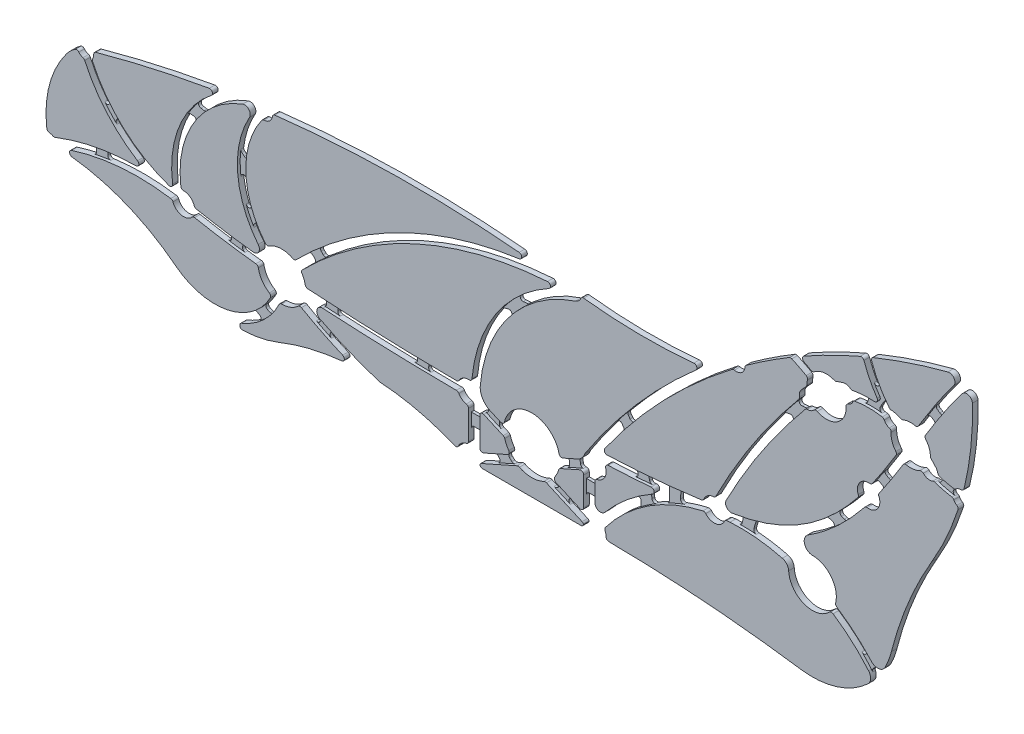
SolidWorks part; units mm, degrees
material "AR-M2"
ref_plane "正面" through (0, 0, 0) normal (0, 0, 1) x (1, 0, 0)
ref_plane "平面" through (0, 0, 0) normal (0, 1, 0) x (1, 0, 0)
ref_plane "右側面" through (0, 0, 0) normal (1, 0, 0) x (0, 0, -1)
sketch "ｽｹｯﾁ1" plane through (0, 0, 0) normal (0, 0, 1) x (1, 0, 0)
  line L1 (-22.5, -10.101) -> (-22.5, 0.101)
  line L2 (-22.5, -10.101) -> (-22.5, 0.101)
  line L3 (22.5, 0.101) -> (22.5, -6.4126)
  line L4 (22.5, 0.101) -> (22.5, -6.4126)
  line L6 (11.119, 1.5832) -> (16.2024, 3.8425)
  line L7 (18.5, -10.042) -> (18.5, 0.042)
  line L8 (8.626, -7.1923) -> (17.0939, -10.9558)
  line L9 (17.0939, 0.9558) -> (10.1663, -2.1231)
  line L10 (18.5, -10.042) -> (18.5, 0.042)
  line L11 (8.626, -7.1923) -> (17.0939, -10.9558)
  line L12 (17.0939, 0.9558) -> (10.1663, -2.1231)
  line L13 (-10.1663, -2.1231) -> (-17.0939, 0.9558)
  line L14 (-17.0939, -10.9558) -> (-8.626, -7.1923)
  line L15 (-18.5, 0.042) -> (-18.5, -10.042)
  line L16 (-10.1663, -2.1231) -> (-17.0939, 0.9558)
  line L17 (-17.0939, -10.9558) -> (-8.626, -7.1923)
  line L18 (-18.5, 0.042) -> (-18.5, -10.042)
  line L19 (-17.5, -16) -> (17.5, -16)
  line L20 (-5.2366, -8.9688) -> (-17.9339, -14.6121)
  line L21 (17.9339, -14.6121) -> (5.2366, -8.9688)
  line L22 (-17.5, -16) -> (17.5, -16)
  line L23 (-5.2366, -8.9688) -> (-17.9339, -14.6121)
  line L24 (17.9339, -14.6121) -> (5.2366, -8.9688)
  line L25 (-14.7807, 3.2107) -> (-11.119, 1.5832)
  line L26 (11.119, 1.5832) -> (16.2024, 3.8425)
  line L27 (-14.7807, 3.2107) -> (-11.119, 1.5832)
  arc A16 (-103.3566, -14.0607) -> (-89.967, -1.5631) centre (-112.8701, 9.5532) ccw
  arc A17 (-89.0603, -0.9998) -> (-89.967, -1.5631) centre (-89.0674, -1.9998) ccw
  arc A18 (-89.0603, -0.9998) -> (-83.2113, 1.2758) centre (-89, 7.5) ccw
  arc A19 (-82.0317, 1.4104) -> (-83.2113, 1.2758) centre (-82.5302, 0.5435) ccw
  arc A20 (-82.0317, 1.4104) -> (-67.3468, -5.898) centre (-13.9413, 119.818) ccw
  arc A21 (-67.6378, -7.8134) -> (-67.3468, -5.898) centre (-67.7378, -6.8184) ccw
  arc A22 (-67.6378, -7.8134) -> (-90.1176, -13.3365) centre (-59.3978, -89.8605) ccw
  arc A23 (-102.9573, -15.9879) -> (-90.1176, -13.3365) centre (-103.9017, 21) ccw
  arc A24 (-103.3566, -14.0607) -> (-102.9573, -15.9879) centre (-102.9829, -14.9883) ccw
  arc A25 (-103.3566, -14.0607) -> (-89.967, -1.5631) centre (-112.8701, 9.5532) ccw
  arc A26 (-89.0603, -0.9998) -> (-89.967, -1.5631) centre (-89.0674, -1.9998) ccw
  arc A27 (-89.0603, -0.9998) -> (-83.2113, 1.2758) centre (-89, 7.5) ccw
  arc A28 (-82.0317, 1.4104) -> (-83.2113, 1.2758) centre (-82.5302, 0.5435) ccw
  arc A29 (-82.0317, 1.4104) -> (-67.3468, -5.898) centre (-13.9413, 119.818) ccw
  arc A30 (-67.6378, -7.8134) -> (-67.3468, -5.898) centre (-67.7378, -6.8184) ccw
  arc A31 (-67.6378, -7.8134) -> (-90.1176, -13.3365) centre (-59.3978, -89.8605) ccw
  arc A32 (-102.9573, -15.9879) -> (-90.1176, -13.3365) centre (-103.9017, 21) ccw
  arc A33 (-103.3566, -14.0607) -> (-102.9573, -15.9879) centre (-102.9829, -14.9883) ccw
  arc A35 (-114.85, 52.6669) -> (-155.2686, 43.5545) centre (-42.29, -363.3692) ccw
  arc A36 (-114.0595, 50.8962) -> (-114.85, 52.6669) centre (-114.6782, 51.6818) ccw
  arc A37 (-114.0595, 50.8962) -> (-127.9008, 16.5808) centre (-91.0356, 21.6602) ccw
  arc A38 (-126.7209, -8.1253) -> (-163.7257, 7.0322) centre (-172, -65.9175) ccw
  arc A39 (-163.9203, 8.9775) -> (-163.7257, 7.0322) centre (-163.613, 8.0259) ccw
  arc A40 (-128.5572, 11.8079) -> (-163.9203, 8.9775) centre (-140.2604, -64.3004) ccw
  arc A41 (-127.7673, 11.1556) -> (-128.5572, 11.8079) centre (-128.7091, 10.8195) ccw
  arc A42 (-127.7673, 11.1556) -> (-121.0036, 9.8502) centre (-124, 12.5) ccw
  arc A43 (-120.0633, 10.1693) -> (-121.0036, 9.8502) centre (-120.2545, 9.1877) ccw
  arc A44 (-120.0633, 10.1693) -> (-98.2474, 6.8503) centre (-69.0994, 271.8045) ccw
  arc A45 (-97.3718, 6.0294) -> (-98.2474, 6.8503) centre (-98.3567, 5.8563) ccw
  arc A46 (-97.3718, 6.0294) -> (-93.4427, 0.2535) centre (-89, 7.5) ccw
  arc A47 (-93.0844, -1.0722) -> (-93.4427, 0.2535) centre (-93.9654, -0.5991) ccw
  arc A48 (-126.7209, -8.1253) -> (-93.0844, -1.0722) centre (-112.8701, 9.5532) ccw
  arc A49 (-126.7209, -8.1253) -> (-163.7257, 7.0322) centre (-172, -65.9175) ccw
  arc A50 (-163.9203, 8.9775) -> (-163.7257, 7.0322) centre (-163.613, 8.0259) ccw
  arc A51 (-128.5572, 11.8079) -> (-163.9203, 8.9775) centre (-140.2604, -64.3004) ccw
  arc A52 (-127.7673, 11.1556) -> (-128.5572, 11.8079) centre (-128.7091, 10.8195) ccw
  arc A53 (-127.7673, 11.1556) -> (-121.0036, 9.8502) centre (-124, 12.5) ccw
  arc A54 (-120.0633, 10.1693) -> (-121.0036, 9.8502) centre (-120.2545, 9.1877) ccw
  arc A55 (-120.0633, 10.1693) -> (-98.2474, 6.8503) centre (-69.0994, 271.8045) ccw
  arc A56 (-97.3718, 6.0294) -> (-98.2474, 6.8503) centre (-98.3567, 5.8563) ccw
  arc A57 (-97.3718, 6.0294) -> (-93.4427, 0.2535) centre (-89, 7.5) ccw
  arc A58 (-93.0844, -1.0722) -> (-93.4427, 0.2535) centre (-93.9654, -0.5991) ccw
  arc A59 (-126.7209, -8.1253) -> (-93.0844, -1.0722) centre (-112.8701, 9.5532) ccw
  arc A60 (-129.2172, 15.4989) -> (-127.9008, 16.5808) centre (-128.8914, 16.4443) ccw
  arc A61 (-156.4002, 40.1644) -> (-129.2172, 15.4989) centre (-114.0417, 59.5347) ccw
  arc A62 (-156.3681, 41.0602) -> (-156.4002, 40.1644) centre (-155.4908, 40.5803) ccw
  arc A63 (-156.3681, 41.0602) -> (-156.0008, 42.5682) centre (-159, 42.5) ccw
  arc A64 (-155.2686, 43.5545) -> (-156.0008, 42.5682) centre (-155.001, 42.5909) ccw
  arc A65 (-114.85, 52.6669) -> (-155.2686, 43.5545) centre (-42.29, -363.3692) ccw
  arc A66 (-114.0595, 50.8962) -> (-114.85, 52.6669) centre (-114.6782, 51.6818) ccw
  arc A67 (-114.0595, 50.8962) -> (-127.9008, 16.5808) centre (-91.0356, 21.6602) ccw
  arc A68 (-129.2172, 15.4989) -> (-127.9008, 16.5808) centre (-128.8914, 16.4443) ccw
  arc A69 (-156.4002, 40.1644) -> (-129.2172, 15.4989) centre (-114.0417, 59.5347) ccw
  arc A70 (-156.3681, 41.0602) -> (-156.4002, 40.1644) centre (-155.4908, 40.5803) ccw
  arc A71 (-156.3681, 41.0602) -> (-156.0008, 42.5682) centre (-159, 42.5) ccw
  arc A72 (-155.2686, 43.5545) -> (-156.0008, 42.5682) centre (-155.001, 42.5909) ccw
  arc A73 (-100.5051, 50.879) -> (-97.4246, 13.2154) centre (-71.0713, 34.3286) ccw
  arc A74 (-99.214, 9.978) -> (-97.4246, 13.2154) centre (-98.9855, 11.9649) ccw
  arc A75 (-4.471, 57.2503) -> (-91.4838, 56.0721) centre (-42.29, -363.3692) ccw
  arc A76 (-140.9263, 15.6997) -> (-169.717, 10.0822) centre (-140.2604, -64.3004) ccw
  arc A77 (-170.5639, 10.1339) -> (-169.717, 10.0822) centre (-170.0852, 11.0119) ccw
  arc A78 (-170.5639, 10.1339) -> (-171.786, 10.4924) centre (-172, 7.5) ccw
  arc A79 (-172.7066, 11.3632) -> (-171.786, 10.4924) centre (-171.7146, 11.4898) ccw
  arc A80 (-165.6353, 37.9447) -> (-172.7066, 11.3632) centre (-136.5587, 15.9784) ccw
  arc A81 (-162.6526, 40.7855) -> (-165.6353, 37.9447) centre (-155.4945, 30.2837) ccw
  arc A82 (-161.317, 40.5944) -> (-162.6526, 40.7855) centre (-162.0894, 39.9592) ccw
  arc A83 (-161.317, 40.5944) -> (-159.8316, 39.6176) centre (-159, 42.5) ccw
  arc A84 (-159.198, 39.0695) -> (-159.8316, 39.6176) centre (-160.1088, 38.6568) ccw
  arc A85 (-159.198, 39.0695) -> (-140.4029, 17.5466) centre (-114.0417, 59.5347) ccw
  arc A86 (-140.9263, 15.6997) -> (-140.4029, 17.5466) centre (-140.9346, 16.6997) ccw
  arc A87 (-140.9263, 15.6997) -> (-169.717, 10.0822) centre (-140.2604, -64.3004) ccw
  arc A88 (-170.5639, 10.1339) -> (-169.717, 10.0822) centre (-170.0852, 11.0119) ccw
  arc A89 (-170.5639, 10.1339) -> (-171.786, 10.4924) centre (-172, 7.5) ccw
  arc A90 (-172.7066, 11.3632) -> (-171.786, 10.4924) centre (-171.7146, 11.4898) ccw
  arc A91 (-165.6353, 37.9447) -> (-172.7066, 11.3632) centre (-136.5587, 15.9784) ccw
  arc A92 (-162.6526, 40.7855) -> (-165.6353, 37.9447) centre (-155.4945, 30.2837) ccw
  arc A93 (-161.317, 40.5944) -> (-162.6526, 40.7855) centre (-162.0894, 39.9592) ccw
  arc A94 (-161.317, 40.5944) -> (-159.8316, 39.6176) centre (-159, 42.5) ccw
  arc A95 (-159.198, 39.0695) -> (-159.8316, 39.6176) centre (-160.1088, 38.6568) ccw
  arc A96 (-159.198, 39.0695) -> (-140.4029, 17.5466) centre (-114.0417, 59.5347) ccw
  arc A97 (-140.9263, 15.6997) -> (-140.4029, 17.5466) centre (-140.9346, 16.6997) ccw
  arc A98 (-4.4224, 55.2639) -> (-4.471, 57.2503) centre (-4.5606, 56.2543) ccw
  arc A99 (-4.4224, 55.2639) -> (-83.9236, 15.238) centre (14.6672, -81.6202) ccw
  arc A100 (-85.0963, 15.0506) -> (-83.9236, 15.238) centre (-84.637, 15.9389) ccw
  arc A101 (-85.0963, 15.0506) -> (-93.5868, 14.6562) centre (-89, 7.5) ccw
  arc A102 (-94.9009, 14.8656) -> (-93.5868, 14.6562) centre (-94.1264, 15.4981) ccw
  arc A103 (-96.1287, 52.1831) -> (-94.9009, 14.8656) centre (-71.0713, 34.3286) ccw
  arc A104 (-95.319, 52.6028) -> (-96.1287, 52.1831) centre (-95.3143, 51.6028) ccw
  arc A105 (-95.319, 52.6028) -> (-92.3587, 55.2099) centre (-95.3328, 55.6027) ccw
  arc A106 (-91.4838, 56.0721) -> (-92.3587, 55.2099) centre (-91.3673, 55.0789) ccw
  arc A107 (-4.471, 57.2503) -> (-91.4838, 56.0721) centre (-42.29, -363.3692) ccw
  arc A108 (-4.4224, 55.2639) -> (-4.471, 57.2503) centre (-4.5606, 56.2543) ccw
  arc A109 (-4.4224, 55.2639) -> (-83.9236, 15.238) centre (14.6672, -81.6202) ccw
  arc A110 (-85.0963, 15.0506) -> (-83.9236, 15.238) centre (-84.637, 15.9389) ccw
  arc A111 (-85.0963, 15.0506) -> (-93.5868, 14.6562) centre (-89, 7.5) ccw
  arc A112 (-94.9009, 14.8656) -> (-93.5868, 14.6562) centre (-94.1264, 15.4981) ccw
  arc A113 (-96.1287, 52.1831) -> (-94.9009, 14.8656) centre (-71.0713, 34.3286) ccw
  arc A114 (-95.319, 52.6028) -> (-96.1287, 52.1831) centre (-95.3143, 51.6028) ccw
  arc A115 (-95.319, 52.6028) -> (-92.3587, 55.2099) centre (-95.3328, 55.6027) ccw
  arc A116 (-91.4838, 56.0721) -> (-92.3587, 55.2099) centre (-91.3673, 55.0789) ccw
  arc A117 (-22.314, 8.9957) -> (-25.9592, 7.0085) centre (-22.5, 5) ccw
  arc A118 (-26.8289, 6.5106) -> (-25.9592, 7.0085) centre (-26.824, 7.5106) ccw
  arc A119 (-79.7472, 8.3552) -> (-26.8289, 6.5106) centre (-22.5, 890.7) ccw
  arc A120 (-80.6633, 9.158) -> (-79.7472, 8.3552) centre (-79.6825, 9.3531) ccw
  arc A121 (-80.6633, 9.158) -> (-81.8017, 12.0204) centre (-89, 7.5) ccw
  arc A122 (-81.6673, 13.2539) -> (-81.8017, 12.0204) centre (-80.9548, 12.5522) ccw
  arc A123 (5.6096, 53.2849) -> (-81.6673, 13.2539) centre (14.6672, -81.6202) ccw
  arc A124 (6.1525, 51.4076) -> (5.6096, 53.2849) centre (5.6766, 52.2871) ccw
  arc A125 (6.1525, 51.4076) -> (-21.2718, 9.9017) centre (31.2679, 5) ccw
  arc A126 (-22.314, 8.9957) -> (-21.2718, 9.9017) centre (-22.2675, 9.9946) ccw
  arc A127 (-22.314, 8.9957) -> (-25.9592, 7.0085) centre (-22.5, 5) ccw
  arc A128 (-26.8289, 6.5106) -> (-25.9592, 7.0085) centre (-26.824, 7.5106) ccw
  arc A129 (-79.7472, 8.3552) -> (-26.8289, 6.5106) centre (-22.5, 890.7) ccw
  arc A130 (-80.6633, 9.158) -> (-79.7472, 8.3552) centre (-79.6825, 9.3531) ccw
  arc A131 (-80.6633, 9.158) -> (-81.8017, 12.0204) centre (-89, 7.5) ccw
  arc A132 (-81.6673, 13.2539) -> (-81.8017, 12.0204) centre (-80.9548, 12.5522) ccw
  arc A133 (5.6096, 53.2849) -> (-81.6673, 13.2539) centre (14.6672, -81.6202) ccw
  arc A134 (6.1525, 51.4076) -> (5.6096, 53.2849) centre (5.6766, 52.2871) ccw
  arc A135 (6.1525, 51.4076) -> (-21.2718, 9.9017) centre (31.2679, 5) ccw
  arc A136 (-22.314, 8.9957) -> (-21.2718, 9.9017) centre (-22.2675, 9.9946) ccw
  arc A137 (-119.4498, 13.1062) -> (-99.214, 9.978) centre (-69.0994, 271.8045) ccw
  arc A138 (-27.4366, -13.8466) -> (-54.0639, -7.5734) centre (-59.3978, -89.8605) ccw
  arc A139 (-54.3014, -7.5287) -> (-54.0639, -7.5734) centre (-53.9993, -6.5755) ccw
  arc A140 (-75.487, 1.2505) -> (-54.3014, -7.5287) centre (-13.9413, 119.818) ccw
  arc A141 (-74.4485, 5.0222) -> (-75.487, 1.2505) centre (-74.5656, 3.0256) ccw
  arc A142 (-74.4485, 5.0222) -> (-26.8313, 3.5106) centre (-22.5, 890.7) ccw
  arc A143 (-25.969, 3.0085) -> (-26.8313, 3.5106) centre (-26.8362, 2.5106) ccw
  arc A144 (-25.969, 3.0085) -> (-23.3, 1.0808) centre (-22.5, 5) ccw
  arc A145 (-22.5, 0.101) -> (-23.3, 1.0808) centre (-23.5, 0.101) ccw
  arc A146 (-23.3, -11.0808) -> (-22.5, -10.101) centre (-23.5, -10.101) ccw
  arc A147 (-23.3, -11.0808) -> (-26.1392, -13.3399) centre (-22.5, -15) ccw
  arc A148 (-27.4366, -13.8466) -> (-26.1392, -13.3399) centre (-27.049, -12.9248) ccw
  arc A149 (-27.4366, -13.8466) -> (-54.0639, -7.5734) centre (-59.3978, -89.8605) ccw
  arc A150 (-54.3014, -7.5287) -> (-54.0639, -7.5734) centre (-53.9993, -6.5755) ccw
  arc A151 (-75.487, 1.2505) -> (-54.3014, -7.5287) centre (-13.9413, 119.818) ccw
  arc A152 (-74.4485, 5.0222) -> (-75.487, 1.2505) centre (-74.5656, 3.0256) ccw
  arc A153 (-74.4485, 5.0222) -> (-26.8313, 3.5106) centre (-22.5, 890.7) ccw
  arc A154 (-25.969, 3.0085) -> (-26.8313, 3.5106) centre (-26.8362, 2.5106) ccw
  arc A155 (-25.969, 3.0085) -> (-23.3, 1.0808) centre (-22.5, 5) ccw
  arc A156 (-22.5, 0.101) -> (-23.3, 1.0808) centre (-23.5, 0.101) ccw
  arc A157 (-23.3, -11.0808) -> (-22.5, -10.101) centre (-23.5, -10.101) ccw
  arc A158 (-23.3, -11.0808) -> (-26.1392, -13.3399) centre (-22.5, -15) ccw
  arc A159 (-27.4366, -13.8466) -> (-26.1392, -13.3399) centre (-27.049, -12.9248) ccw
  arc A160 (-120.207, 13.7702) -> (-119.4498, 13.1062) centre (-119.2588, 14.0878) ccw
  arc A161 (-120.207, 13.7702) -> (-123.99, 16.5) centre (-124, 12.5) ccw
  arc A162 (-124.9796, 17.3747) -> (-123.99, 16.5) centre (-123.9875, 17.5) ccw
  arc A163 (-102.9446, 53.7342) -> (-124.9796, 17.3747) centre (-91.0356, 21.6602) ccw
  arc A164 (-100.5051, 50.879) -> (-102.9446, 53.7342) centre (-102.2484, 51.8592) ccw
  arc A165 (-100.5051, 50.879) -> (-97.4246, 13.2154) centre (-71.0713, 34.3286) ccw
  arc A166 (-99.214, 9.978) -> (-97.4246, 13.2154) centre (-98.9855, 11.9649) ccw
  arc A167 (-119.4498, 13.1062) -> (-99.214, 9.978) centre (-69.0994, 271.8045) ccw
  arc A168 (-120.207, 13.7702) -> (-119.4498, 13.1062) centre (-119.2588, 14.0878) ccw
  arc A169 (-120.207, 13.7702) -> (-123.99, 16.5) centre (-124, 12.5) ccw
  arc A170 (-124.9796, 17.3747) -> (-123.99, 16.5) centre (-123.9875, 17.5) ccw
  arc A171 (-102.9446, 53.7342) -> (-124.9796, 17.3747) centre (-91.0356, 21.6602) ccw
  arc A172 (-100.5051, 50.879) -> (-102.9446, 53.7342) centre (-102.2484, 51.8592) ccw
  arc A180 (17.0939, -10.9558) -> (18.5, -10.042) centre (17.5, -10.042) ccw
  arc A181 (8.2111, -5.7077) -> (8.626, -7.1923) centre (9.0322, -6.2785) ccw
  arc A182 (22.5, -6.4126) -> (26.0294, -7.7013) centre (24.5, -6.4126) ccw
  arc A183 (23.3, 1.0808) -> (22.5, 0.101) centre (23.5, 0.101) ccw
  arc A184 (23.3, 1.0808) -> (26.3403, 6.1191) centre (22.5, 5) ccw
  arc A185 (27.2601, 7.398) -> (26.3403, 6.1191) centre (27.3003, 6.3988) ccw
  arc A186 (27.2601, 7.398) -> (42.5161, 8.3479) centre (13.2682, 355.1295) ccw
  arc A187 (43.0938, 6.4818) -> (42.5161, 8.3479) centre (42.6001, 7.3514) ccw
  arc A188 (107.7452, 73.9205) -> (100.6016, 72.9268) centre (105, 67.4812) ccw
  arc A189 (99.4771, 72.8365) -> (100.6016, 72.9268) centre (99.9733, 73.7047) ccw
  arc A190 (99.4771, 72.8365) -> (96.9768, 74.198) centre (65, 12.5) ccw
  arc A191 (96.9469, 75.9576) -> (96.9768, 74.198) centre (97.4369, 75.0859) ccw
  arc A192 (116.993, 85.9037) -> (96.9469, 75.9576) centre (203.2901, -113.1988) ccw
  arc A193 (118.3344, 85.3171) -> (116.993, 85.9037) centre (117.3907, 84.9862) ccw
  arc A194 (118.3344, 85.3171) -> (122.9876, 76.0572) centre (156.5, 98.6967) ccw
  arc A195 (122.0896, 74.4999) -> (122.9876, 76.0572) centre (122.1589, 75.4974) ccw
  arc A196 (122.0896, 74.4999) -> (114.3306, 74.0344) centre (120, 44.4324) ccw
  arc A197 (113.5331, 74.2236) -> (114.3306, 74.0344) centre (114.1425, 75.0165) ccw
  arc A198 (113.5331, 74.2236) -> (110.8362, 74.7163) centre (111.7051, 71.8449) ccw
  arc A199 (110.8362, 74.7163) -> (108.5008, 73.9088) centre (120, 44.4324) ccw
  arc A200 (107.7452, 73.9205) -> (108.5008, 73.9088) centre (108.1373, 74.8404) ccw
  arc A201 (107.7452, 73.9205) -> (100.6016, 72.9268) centre (105, 67.4812) ccw
  arc A202 (99.4771, 72.8365) -> (100.6016, 72.9268) centre (99.9733, 73.7047) ccw
  arc A203 (99.4771, 72.8365) -> (96.9768, 74.198) centre (65, 12.5) ccw
  arc A204 (96.9469, 75.9576) -> (96.9768, 74.198) centre (97.4369, 75.0859) ccw
  arc A205 (116.993, 85.9037) -> (96.9469, 75.9576) centre (203.2901, -113.1988) ccw
  arc A206 (118.3344, 85.3171) -> (116.993, 85.9037) centre (117.3907, 84.9862) ccw
  arc A207 (118.3344, 85.3171) -> (122.9876, 76.0572) centre (156.5, 98.6967) ccw
  arc A208 (122.0896, 74.4999) -> (122.9876, 76.0572) centre (122.1589, 75.4974) ccw
  arc A209 (122.0896, 74.4999) -> (114.3306, 74.0344) centre (120, 44.4324) ccw
  arc A210 (113.5331, 74.2236) -> (114.3306, 74.0344) centre (114.1425, 75.0165) ccw
  arc A211 (113.5331, 74.2236) -> (110.8362, 74.7163) centre (111.7051, 71.8449) ccw
  arc A212 (110.8362, 74.7163) -> (108.5008, 73.9088) centre (120, 44.4324) ccw
  arc A213 (107.7452, 73.9205) -> (108.5008, 73.9088) centre (108.1373, 74.8404) ccw
  arc A214 (43.0938, 6.4818) -> (26.0294, -7.7013) centre (74.1755, -48.2713) ccw
  arc A215 (22.5, -6.4126) -> (26.0294, -7.7013) centre (24.5, -6.4126) ccw
  arc A216 (23.3, 1.0808) -> (22.5, 0.101) centre (23.5, 0.101) ccw
  arc A217 (23.3, 1.0808) -> (26.3403, 6.1191) centre (22.5, 5) ccw
  arc A218 (89.2736, 9.7568) -> (70.6824, 11.5869) centre (74.1755, -48.2713) ccw
  arc A219 (91.5134, 7.0221) -> (89.2736, 9.7568) centre (88.5182, 6.8535) ccw
  arc A220 (91.5134, 7.0221) -> (106.0705, 1.5503) centre (100, 7.5) ccw
  arc A221 (107.3377, 1.6835) -> (106.0705, 1.5503) centre (106.7847, 0.8503) ccw
  arc A222 (120.0008, -9.6028) -> (107.3377, 1.6835) centre (74.1755, -48.2713) ccw
  arc A223 (119.7512, -13.7341) -> (120.0008, -9.6028) centre (117.708, -11.5375) ccw
  arc A224 (95.9045, -21.2094) -> (119.7512, -13.7341) centre (100, 7.5) ccw
  arc A225 (95.9045, -21.2094) -> (27.4903, -16.024) centre (22.5, -535.7727) ccw
  arc A226 (26.5, -15.0192) -> (27.4903, -16.024) centre (27.4999, -15.024) ccw
  arc A227 (26.5, -15.0192) -> (26.1198, -13.2978) centre (22.5, -15) ccw
  arc A228 (26.225, -12.2719) -> (26.1198, -13.2978) centre (27.0247, -12.8723) ccw
  arc A229 (60.9851, 10.2199) -> (26.225, -12.2719) centre (74.1755, -48.2713) ccw
  arc A230 (61.9641, 9.8955) -> (60.9851, 10.2199) centre (61.2051, 9.2444) ccw
  arc A231 (61.9641, 9.8955) -> (68.6424, 10.8468) centre (65, 12.5) ccw
  arc A232 (69.4305, 11.426) -> (68.6424, 10.8468) centre (69.553, 10.4335) ccw
  arc A233 (69.4305, 11.426) -> (70.604, 11.5793) centre (59.3082, 93.4746) ccw
  arc A234 (70.6824, 11.5869) -> (70.604, 11.5793) centre (70.7407, 10.5886) ccw
  arc A235 (89.2736, 9.7568) -> (70.6824, 11.5869) centre (74.1755, -48.2713) ccw
  arc A236 (91.5134, 7.0221) -> (89.2736, 9.7568) centre (88.5182, 6.8535) ccw
  arc A237 (91.5134, 7.0221) -> (106.0705, 1.5503) centre (100, 7.5) ccw
  arc A238 (107.3377, 1.6835) -> (106.0705, 1.5503) centre (106.7847, 0.8503) ccw
  arc A239 (120.0008, -9.6028) -> (107.3377, 1.6835) centre (74.1755, -48.2713) ccw
  arc A240 (119.7512, -13.7341) -> (120.0008, -9.6028) centre (117.708, -11.5375) ccw
  arc A241 (95.9045, -21.2094) -> (119.7512, -13.7341) centre (100, 7.5) ccw
  arc A242 (95.9045, -21.2094) -> (27.4903, -16.024) centre (22.5, -535.7727) ccw
  arc A243 (26.5, -15.0192) -> (27.4903, -16.024) centre (27.4999, -15.024) ccw
  arc A244 (26.5, -15.0192) -> (26.1198, -13.2978) centre (22.5, -15) ccw
  arc A245 (26.225, -12.2719) -> (26.1198, -13.2978) centre (27.0247, -12.8723) ccw
  arc A246 (60.9851, 10.2199) -> (26.225, -12.2719) centre (74.1755, -48.2713) ccw
  arc A247 (61.9641, 9.8955) -> (60.9851, 10.2199) centre (61.2051, 9.2444) ccw
  arc A248 (61.9641, 9.8955) -> (68.6424, 10.8468) centre (65, 12.5) ccw
  arc A249 (69.4305, 11.426) -> (68.6424, 10.8468) centre (69.553, 10.4335) ccw
  arc A250 (69.4305, 11.426) -> (70.604, 11.5793) centre (59.3082, 93.4746) ccw
  arc A251 (70.6824, 11.5869) -> (70.604, 11.5793) centre (70.7407, 10.5886) ccw
  arc A252 (27.2601, 7.398) -> (26.3403, 6.1191) centre (27.3003, 6.3988) ccw
  arc A253 (27.2601, 7.398) -> (42.5161, 8.3479) centre (13.2682, 355.1295) ccw
  arc A254 (71.3431, 59.0772) -> (26.022, 11.9612) centre (203.2901, -113.1988) ccw
  arc A255 (72.1979, 59.2524) -> (71.3431, 59.0772) centre (71.9512, 58.2833) ccw
  arc A256 (72.1979, 59.2524) -> (75.9352, 62.0305) centre (72.938, 62.1596) ccw
  arc A257 (76.3493, 62.7985) -> (75.9352, 62.0305) centre (76.9343, 61.9874) ccw
  arc A258 (91.7165, 72.9204) -> (76.3493, 62.7985) centre (203.2901, -113.1988) ccw
  arc A259 (92.6465, 72.9722) -> (91.7165, 72.9204) centre (92.2307, 72.0627) ccw
  arc A260 (97.7506, 70.3671) -> (92.6465, 72.9722) centre (65, 12.5) ccw
  arc A261 (98.2258, 69.2449) -> (97.7506, 70.3671) centre (97.2581, 69.4969) ccw
  arc A262 (98.2258, 69.2449) -> (98.0007, 67.5789) centre (105, 67.4812) ccw
  arc A263 (97.7054, 66.8832) -> (98.0007, 67.5789) centre (97.0008, 67.5928) ccw
  arc A264 (97.7054, 66.8832) -> (96.0213, 65.0748) centre (120, 44.4324) ccw
  arc A265 (96.0213, 65.0748) -> (95.3497, 62.5466) centre (98.2949, 63.1176) ccw
  arc A266 (95.1344, 61.7139) -> (95.3497, 62.5466) centre (94.368, 62.3562) ccw
  arc A267 (95.1344, 61.7139) -> (65.5834, 17.0366) centre (276.8279, -90.5756) ccw
  arc A268 (64.7539, 16.4924) -> (65.5834, 17.0366) centre (64.6924, 17.4905) ccw
  arc A269 (64.7539, 16.4924) -> (61.2853, 13.9837) centre (65, 12.5) ccw
  arc A270 (60.4936, 13.364) -> (61.2853, 13.9837) centre (60.3567, 14.3546) ccw
  arc A271 (26.8783, 10.3852) -> (60.4936, 13.364) centre (13.2682, 355.1295) ccw
  arc A272 (26.022, 11.9612) -> (26.8783, 10.3852) centre (26.8389, 11.3844) ccw
  arc A273 (71.3431, 59.0772) -> (26.022, 11.9612) centre (203.2901, -113.1988) ccw
  arc A274 (72.1979, 59.2524) -> (71.3431, 59.0772) centre (71.9512, 58.2833) ccw
  arc A275 (72.1979, 59.2524) -> (75.9352, 62.0305) centre (72.938, 62.1596) ccw
  arc A276 (76.3493, 62.7985) -> (75.9352, 62.0305) centre (76.9343, 61.9874) ccw
  arc A277 (91.7165, 72.9204) -> (76.3493, 62.7985) centre (203.2901, -113.1988) ccw
  arc A278 (92.6465, 72.9722) -> (91.7165, 72.9204) centre (92.2307, 72.0627) ccw
  arc A279 (97.7506, 70.3671) -> (92.6465, 72.9722) centre (65, 12.5) ccw
  arc A280 (98.2258, 69.2449) -> (97.7506, 70.3671) centre (97.2581, 69.4969) ccw
  arc A281 (98.2258, 69.2449) -> (98.0007, 67.5789) centre (105, 67.4812) ccw
  arc A282 (97.7054, 66.8832) -> (98.0007, 67.5789) centre (97.0008, 67.5928) ccw
  arc A283 (97.7054, 66.8832) -> (96.0213, 65.0748) centre (120, 44.4324) ccw
  arc A284 (96.0213, 65.0748) -> (95.3497, 62.5466) centre (98.2949, 63.1176) ccw
  arc A285 (95.1344, 61.7139) -> (95.3497, 62.5466) centre (94.368, 62.3562) ccw
  arc A286 (95.1344, 61.7139) -> (65.5834, 17.0366) centre (276.8279, -90.5756) ccw
  arc A287 (64.7539, 16.4924) -> (65.5834, 17.0366) centre (64.6924, 17.4905) ccw
  arc A288 (64.7539, 16.4924) -> (61.2853, 13.9837) centre (65, 12.5) ccw
  arc A289 (60.4936, 13.364) -> (61.2853, 13.9837) centre (60.3567, 14.3546) ccw
  arc A290 (26.8783, 10.3852) -> (60.4936, 13.364) centre (13.2682, 355.1295) ccw
  arc A291 (26.022, 11.9612) -> (26.8783, 10.3852) centre (26.8389, 11.3844) ccw
  arc A292 (43.0938, 6.4818) -> (42.5161, 8.3479) centre (42.6001, 7.3514) ccw
  arc A293 (43.0938, 6.4818) -> (26.0294, -7.7013) centre (74.1755, -48.2713) ccw
  arc A294 (8.2111, -5.7077) -> (9.6113, -2.7608) centre (0, 0) ccw
  arc A295 (10.1663, -2.1231) -> (9.6113, -2.7608) centre (10.5725, -3.0369) ccw
  arc A296 (18.5, 0.042) -> (17.0939, 0.9558) centre (17.5, 0.042) ccw
  arc A297 (148.2331, 96.7006) -> (121.6343, 87.8518) centre (203.2901, -113.1988) ccw
  arc A298 (150.3263, 93.5472) -> (148.2331, 96.7006) centre (148.7406, 94.766) ccw
  arc A302 (136.5911, 74.298) -> (137.6701, 74.7478) centre (136.8184, 75.2718) ccw
  arc A303 (136.5911, 74.298) -> (132.2548, 73.9205) centre (135, 67.4812) ccw
  arc A304 (131.4992, 73.9088) -> (132.2548, 73.9205) centre (131.8627, 74.8404) ccw
  arc A305 (131.4992, 73.9088) -> (129.1638, 74.7163) centre (120, 44.4324) ccw
  arc A306 (129.1638, 74.7163) -> (128.1602, 74.8418) centre (128.2949, 71.8449) ccw
  arc A307 (127.3364, 75.2137) -> (128.1602, 74.8418) centre (128.1152, 75.8408) ccw
  arc A308 (69.2577, 17.6177) -> (71.3333, 14.7162) centre (71.0313, 16.6932) ccw
  arc A309 (97.4124, 59.7615) -> (69.2577, 17.6177) centre (276.8279, -90.5756) ccw
  arc A310 (98.2079, 60.1189) -> (97.4124, 59.7615) centre (98.1789, 59.1193) ccw
  arc A311 (98.2079, 60.1189) -> (100.5079, 61.0921) centre (98.2949, 63.1176) ccw
  arc A312 (101.7149, 61.3) -> (100.5079, 61.0921) centre (101.2456, 60.4169) ccw
  arc A313 (101.7149, 61.3) -> (111.9821, 67.9818) centre (105, 67.4812) ccw
  arc A314 (112.6609, 69.0012) -> (111.9821, 67.9818) centre (112.9795, 68.0533) ccw
  arc A315 (112.6609, 69.0012) -> (114.4231, 70.575) centre (111.7051, 71.8449) ccw
  arc A316 (115.1504, 71.1356) -> (114.4231, 70.575) centre (115.3291, 70.1517) ccw
  arc A317 (124.8496, 71.1356) -> (115.1504, 71.1356) centre (120, 44.4324) ccw
  arc A318 (125.5769, 70.575) -> (124.8496, 71.1356) centre (124.6709, 70.1517) ccw
  arc A319 (125.5769, 70.575) -> (127.3391, 69.0012) centre (128.2949, 71.8449) ccw
  arc A320 (128.0179, 67.9818) -> (127.3391, 69.0012) centre (127.0205, 68.0533) ccw
  arc A321 (128.0179, 67.9818) -> (129.6706, 62.9428) centre (135, 67.4812) ccw
  arc A322 (129.7605, 61.7697) -> (129.6706, 62.9428) centre (128.9093, 62.2944) ccw
  arc A323 (120.4118, 48.4111) -> (121.3328, 48.8307) centre (120.5147, 49.4058) ccw
  arc A324 (120.4118, 48.4111) -> (116.299, 42.915) centre (120, 44.4324) ccw
  arc A325 (116.1539, 41.9101) -> (116.299, 42.915) centre (115.3737, 42.5356) ccw
  arc A326 (69.2577, 17.6177) -> (71.3333, 14.7162) centre (71.0313, 16.6932) ccw
  arc A327 (97.4124, 59.7615) -> (69.2577, 17.6177) centre (276.8279, -90.5756) ccw
  arc A328 (98.2079, 60.1189) -> (97.4124, 59.7615) centre (98.1789, 59.1193) ccw
  arc A329 (98.2079, 60.1189) -> (100.5079, 61.0921) centre (98.2949, 63.1176) ccw
  arc A330 (101.7149, 61.3) -> (100.5079, 61.0921) centre (101.2456, 60.4169) ccw
  arc A331 (101.7149, 61.3) -> (111.9821, 67.9818) centre (105, 67.4812) ccw
  arc A332 (112.6609, 69.0012) -> (111.9821, 67.9818) centre (112.9795, 68.0533) ccw
  arc A333 (112.6609, 69.0012) -> (114.4231, 70.575) centre (111.7051, 71.8449) ccw
  arc A334 (115.1504, 71.1356) -> (114.4231, 70.575) centre (115.3291, 70.1517) ccw
  arc A335 (124.8496, 71.1356) -> (115.1504, 71.1356) centre (120, 44.4324) ccw
  arc A336 (125.5769, 70.575) -> (124.8496, 71.1356) centre (124.6709, 70.1517) ccw
  arc A337 (125.5769, 70.575) -> (127.3391, 69.0012) centre (128.2949, 71.8449) ccw
  arc A338 (128.0179, 67.9818) -> (127.3391, 69.0012) centre (127.0205, 68.0533) ccw
  arc A339 (128.0179, 67.9818) -> (129.6706, 62.9428) centre (135, 67.4812) ccw
  arc A340 (129.7605, 61.7697) -> (129.6706, 62.9428) centre (128.9093, 62.2944) ccw
  arc A341 (120.4118, 48.4111) -> (121.3328, 48.8307) centre (120.5147, 49.4058) ccw
  arc A342 (120.4118, 48.4111) -> (116.299, 42.915) centre (120, 44.4324) ccw
  arc A343 (116.1539, 41.9101) -> (116.299, 42.915) centre (115.3737, 42.5356) ccw
  arc A344 (121.0642, 86.6023) -> (127.3364, 75.2137) centre (156.5, 98.6967) ccw
  arc A345 (121.6343, 87.8518) -> (121.0642, 86.6023) centre (122.0106, 86.9253) ccw
  arc A346 (148.2331, 96.7006) -> (121.6343, 87.8518) centre (203.2901, -113.1988) ccw
  arc A347 (150.3263, 93.5472) -> (148.2331, 96.7006) centre (148.7406, 94.766) ccw
  arc A348 (136.5911, 74.298) -> (137.6701, 74.7478) centre (136.8184, 75.2718) ccw
  arc A349 (136.5911, 74.298) -> (132.2548, 73.9205) centre (135, 67.4812) ccw
  arc A350 (131.4992, 73.9088) -> (132.2548, 73.9205) centre (131.8627, 74.8404) ccw
  arc A351 (131.4992, 73.9088) -> (129.1638, 74.7163) centre (120, 44.4324) ccw
  arc A352 (129.1638, 74.7163) -> (128.1602, 74.8418) centre (128.2949, 71.8449) ccw
  arc A353 (127.3364, 75.2137) -> (128.1602, 74.8418) centre (128.1152, 75.8408) ccw
  arc A354 (121.0642, 86.6023) -> (127.3364, 75.2137) centre (156.5, 98.6967) ccw
  arc A355 (121.6343, 87.8518) -> (121.0642, 86.6023) centre (122.0106, 86.9253) ccw
  arc A356 (17.0939, -10.9558) -> (18.5, -10.042) centre (17.5, -10.042) ccw
  arc A357 (8.2111, -5.7077) -> (8.626, -7.1923) centre (9.0322, -6.2785) ccw
  arc A358 (8.2111, -5.7077) -> (9.6113, -2.7608) centre (0, 0) ccw
  arc A359 (10.1663, -2.1231) -> (9.6113, -2.7608) centre (10.5725, -3.0369) ccw
  arc A360 (18.5, 0.042) -> (17.0939, 0.9558) centre (17.5, 0.042) ccw
  arc A361 (-9.6113, -2.7608) -> (-10.1663, -2.1231) centre (-10.5725, -3.0369) ccw
  arc A362 (-9.6113, -2.7608) -> (-8.2111, -5.7077) centre (0, 0) ccw
  arc A363 (-8.626, -7.1923) -> (-8.2111, -5.7077) centre (-9.0322, -6.2785) ccw
  arc A364 (-18.5, -10.042) -> (-17.0939, -10.9558) centre (-17.5, -10.042) ccw
  arc A365 (-17.0939, 0.9558) -> (-18.5, 0.042) centre (-17.5, 0.042) ccw
  arc A366 (-9.6113, -2.7608) -> (-10.1663, -2.1231) centre (-10.5725, -3.0369) ccw
  arc A367 (-9.6113, -2.7608) -> (-8.2111, -5.7077) centre (0, 0) ccw
  arc A368 (-8.626, -7.1923) -> (-8.2111, -5.7077) centre (-9.0322, -6.2785) ccw
  arc A369 (-18.5, -10.042) -> (-17.0939, -10.9558) centre (-17.5, -10.042) ccw
  arc A370 (-17.0939, 0.9558) -> (-18.5, 0.042) centre (-17.5, 0.042) ccw
  circle A371 centre (72.938, 62.1596) radius 1.6
  circle A372 centre (72.938, 62.1596) radius 1.6 construction
  arc A373 (18.4772, -15.2121) -> (17.9339, -14.6121) centre (17.5277, -15.5259) ccw
  arc A374 (17.5, -16) -> (18.4772, -15.2121) centre (17.5, -15) ccw
  arc A375 (-18.4772, -15.2121) -> (-17.5, -16) centre (-17.5, -15) ccw
  arc A376 (-17.9339, -14.6121) -> (-18.4772, -15.2121) centre (-17.5277, -15.5259) ccw
  arc A377 (-4.3913, -8.9842) -> (-5.2366, -8.9688) centre (-4.8304, -9.8827) ccw
  arc A378 (-4.3913, -8.9842) -> (4.3913, -8.9842) centre (0, 0) ccw
  arc A379 (5.2366, -8.9688) -> (4.3913, -8.9842) centre (4.8304, -9.8827) ccw
  arc A380 (18.4772, -15.2121) -> (17.9339, -14.6121) centre (17.5277, -15.5259) ccw
  arc A381 (17.5, -16) -> (18.4772, -15.2121) centre (17.5, -15) ccw
  arc A382 (-18.4772, -15.2121) -> (-17.5, -16) centre (-17.5, -15) ccw
  arc A383 (-17.9339, -14.6121) -> (-18.4772, -15.2121) centre (-17.5277, -15.5259) ccw
  arc A384 (-4.3913, -8.9842) -> (-5.2366, -8.9688) centre (-4.8304, -9.8827) ccw
  arc A385 (-4.3913, -8.9842) -> (4.3913, -8.9842) centre (0, 0) ccw
  arc A386 (5.2366, -8.9688) -> (4.3913, -8.9842) centre (4.8304, -9.8827) ccw
  arc A392 (15.611, 52.2409) -> (17.4557, 53.9822) centre (14.6672, 55.0886) ccw
  arc A393 (18.4998, 54.6068) -> (17.4557, 53.9822) centre (18.3852, 53.6134) ccw
  arc A394 (18.4998, 54.6068) -> (57.7478, 54.1867) centre (40.1338, 242.1889) ccw
  arc A395 (58.4992, 52.4382) -> (57.7478, 54.1867) centre (57.841, 53.1911) ccw
  arc A396 (58.4992, 52.4382) -> (19.152, 7.1889) centre (203.2901, -113.1988) ccw
  arc A397 (19.152, 7.1889) -> (18.7985, 6.5163) centre (22.5, 5) ccw
  arc A398 (16.2024, 3.8425) -> (18.7985, 6.5163) centre (14.1717, 8.4116) ccw
  arc A399 (9.7389, 2.27) -> (11.119, 1.5832) centre (10.7128, 2.4971) ccw
  arc A400 (9.7389, 2.27) -> (-9.7389, 2.27) centre (0, 0) ccw
  arc A401 (-11.119, 1.5832) -> (-9.7389, 2.27) centre (-10.7128, 2.4971) ccw
  arc A402 (-18.3225, 9.1999) -> (-14.7807, 3.2107) centre (-12.3439, 8.6935) ccw
  arc A403 (15.611, 52.2409) -> (-18.3225, 9.1999) centre (31.2679, 5) ccw
  arc A404 (15.611, 52.2409) -> (17.4557, 53.9822) centre (14.6672, 55.0886) ccw
  arc A405 (18.4998, 54.6068) -> (17.4557, 53.9822) centre (18.3852, 53.6134) ccw
  arc A406 (18.4998, 54.6068) -> (57.7478, 54.1867) centre (40.1338, 242.1889) ccw
  arc A407 (58.4992, 52.4382) -> (57.7478, 54.1867) centre (57.841, 53.1911) ccw
  arc A408 (58.4992, 52.4382) -> (19.152, 7.1889) centre (203.2901, -113.1988) ccw
  arc A409 (19.152, 7.1889) -> (18.7985, 6.5163) centre (22.5, 5) ccw
  arc A410 (16.2024, 3.8425) -> (18.7985, 6.5163) centre (14.1717, 8.4116) ccw
  arc A411 (9.7389, 2.27) -> (11.119, 1.5832) centre (10.7128, 2.4971) ccw
  arc A412 (9.7389, 2.27) -> (-9.7389, 2.27) centre (0, 0) ccw
  arc A413 (-11.119, 1.5832) -> (-9.7389, 2.27) centre (-10.7128, 2.4971) ccw
  arc A414 (-18.3225, 9.1999) -> (-14.7807, 3.2107) centre (-12.3439, 8.6935) ccw
  arc A415 (15.611, 52.2409) -> (-18.3225, 9.1999) centre (31.2679, 5) ccw
  arc A416 (153.9743, 63.4967) -> (156.9587, 91.4184) centre (52.35, 88.479) ccw
  arc A417 (152.9962, 62.7355) -> (153.9743, 63.4967) centre (153.0032, 63.7354) ccw
  arc A418 (152.9962, 62.7355) -> (151.0229, 62.0134) centre (152.9752, 59.7355) ccw
  arc A419 (150.204, 61.7869) -> (151.0229, 62.0134) centre (150.3722, 62.7727) ccw
  arc A420 (145.3266, 62.9598) -> (150.204, 61.7869) centre (156.5, 98.6967) ccw
  arc A421 (144.645, 63.7151) -> (145.3266, 62.9598) centre (145.625, 63.9142) ccw
  arc A422 (144.645, 63.7151) -> (143.9787, 65.0748) centre (141.7051, 63.1176) ccw
  arc A423 (143.9787, 65.0748) -> (142.2946, 66.8832) centre (120, 44.4324) ccw
  arc A424 (141.9993, 67.5789) -> (142.2946, 66.8832) centre (142.9992, 67.5928) ccw
  arc A425 (141.9993, 67.5789) -> (140.3274, 72.022) centre (135, 67.4812) ccw
  arc A426 (140.2368, 73.1947) -> (140.3274, 72.022) centre (141.0885, 72.6707) ccw
  arc A427 (156.9587, 91.4184) -> (153.3843, 92.5946) centre (154.9595, 91.3622) ccw
  arc A428 (153.9743, 63.4967) -> (156.9587, 91.4184) centre (52.35, 88.479) ccw
  arc A429 (152.9962, 62.7355) -> (153.9743, 63.4967) centre (153.0032, 63.7354) ccw
  arc A430 (152.9962, 62.7355) -> (151.0229, 62.0134) centre (152.9752, 59.7355) ccw
  arc A431 (150.204, 61.7869) -> (151.0229, 62.0134) centre (150.3722, 62.7727) ccw
  arc A432 (145.3266, 62.9598) -> (150.204, 61.7869) centre (156.5, 98.6967) ccw
  arc A433 (144.645, 63.7151) -> (145.3266, 62.9598) centre (145.625, 63.9142) ccw
  arc A434 (144.645, 63.7151) -> (143.9787, 65.0748) centre (141.7051, 63.1176) ccw
  arc A435 (143.9787, 65.0748) -> (142.2946, 66.8832) centre (120, 44.4324) ccw
  arc A436 (141.9993, 67.5789) -> (142.2946, 66.8832) centre (142.9992, 67.5928) ccw
  arc A437 (141.9993, 67.5789) -> (140.3274, 72.022) centre (135, 67.4812) ccw
  arc A438 (140.2368, 73.1947) -> (140.3274, 72.022) centre (141.0885, 72.6707) ccw
  arc A439 (156.9587, 91.4184) -> (153.3843, 92.5946) centre (154.9595, 91.3622) ccw
  arc A448 (143.571, 60.3761) -> (149.6129, 58.8445) centre (156.5, 98.6967) ccw
  arc A449 (150.3258, 58.3282) -> (149.6129, 58.8445) centre (149.4426, 57.8591) ccw
  arc A450 (150.3258, 58.3282) -> (151.4085, 57.1771) centre (152.9752, 59.7355) ccw
  arc A451 (151.8369, 56.0141) -> (151.4085, 57.1771) centre (150.8863, 56.3243) ccw
  arc A452 (142.5363, 35.3937) -> (151.8369, 56.0141) centre (52.35, 88.479) ccw
  arc A453 (142.5363, 35.3937) -> (128.1038, 0.346) centre (258.447, -32.8336) ccw
  arc A454 (125.9109, -5.5239) -> (128.1038, 0.346) centre (100, 7.5) ccw
  arc A455 (120.9994, -6.1821) -> (125.9109, -5.5239) centre (123.2305, -4.1766) ccw
  arc A456 (120.9994, -6.1821) -> (108.6769, 4.3939) centre (74.1755, -48.2713) ccw
  arc A457 (108.2539, 5.4693) -> (108.6769, 4.3939) centre (109.2249, 5.2304) ccw
  arc A463 (108.2539, 5.4693) -> (100.0397, 15.9999) centre (100, 7.5) ccw
  arc A464 (98.4481, 21.534) -> (100.0397, 15.9999) centre (100.0538, 18.9999) ccw
  arc A465 (119.4644, 40.4684) -> (118.5498, 40.1024) centre (119.3305, 39.4774) ccw
  arc A466 (119.4644, 40.4684) -> (123.6518, 46.0647) centre (120, 44.4324) ccw
  arc A467 (123.7469, 47.0482) -> (123.6518, 46.0647) centre (124.5647, 46.4728) ccw
  arc A468 (133.4061, 60.6651) -> (132.3271, 60.2161) centre (133.1784, 59.6914) ccw
  arc A469 (133.4061, 60.6651) -> (138.2851, 61.3) centre (135, 67.4812) ccw
  arc A470 (139.4921, 61.0921) -> (138.2851, 61.3) centre (138.7544, 60.4169) ccw
  arc A471 (139.4921, 61.0921) -> (142.8648, 60.3508) centre (141.7051, 63.1176) ccw
  arc A472 (143.571, 60.3761) -> (142.8648, 60.3508) centre (143.2514, 59.4285) ccw
  arc A473 (143.571, 60.3761) -> (149.6129, 58.8445) centre (156.5, 98.6967) ccw
  arc A474 (150.3258, 58.3282) -> (149.6129, 58.8445) centre (149.4426, 57.8591) ccw
  arc A475 (150.3258, 58.3282) -> (151.4085, 57.1771) centre (152.9752, 59.7355) ccw
  arc A476 (151.8369, 56.0141) -> (151.4085, 57.1771) centre (150.8863, 56.3243) ccw
  arc A477 (142.5363, 35.3937) -> (151.8369, 56.0141) centre (52.35, 88.479) ccw
  arc A478 (142.5363, 35.3937) -> (128.1038, 0.346) centre (258.447, -32.8336) ccw
  arc A479 (125.9109, -5.5239) -> (128.1038, 0.346) centre (100, 7.5) ccw
  arc A480 (120.9994, -6.1821) -> (125.9109, -5.5239) centre (123.2305, -4.1766) ccw
  arc A481 (120.9994, -6.1821) -> (108.6769, 4.3939) centre (74.1755, -48.2713) ccw
  arc A482 (108.2539, 5.4693) -> (108.6769, 4.3939) centre (109.2249, 5.2304) ccw
  arc A483 (108.2539, 5.4693) -> (100.0397, 15.9999) centre (100, 7.5) ccw
  arc A484 (98.4481, 21.534) -> (100.0397, 15.9999) centre (100.0538, 18.9999) ccw
  arc A485 (119.4644, 40.4684) -> (118.5498, 40.1024) centre (119.3305, 39.4774) ccw
  arc A486 (119.4644, 40.4684) -> (123.6518, 46.0647) centre (120, 44.4324) ccw
  arc A487 (123.7469, 47.0482) -> (123.6518, 46.0647) centre (124.5647, 46.4728) ccw
  arc A488 (133.4061, 60.6651) -> (132.3271, 60.2161) centre (133.1784, 59.6914) ccw
  arc A489 (133.4061, 60.6651) -> (138.2851, 61.3) centre (135, 67.4812) ccw
  arc A490 (139.4921, 61.0921) -> (138.2851, 61.3) centre (138.7544, 60.4169) ccw
  arc A491 (139.4921, 61.0921) -> (142.8648, 60.3508) centre (141.7051, 63.1176) ccw
  arc A492 (143.571, 60.3761) -> (142.8648, 60.3508) centre (143.2514, 59.4285) ccw
  spline S1 degree 3 poles (-2131.8437, 2012.1001) (110.6902, -268.7552) (19.6333, 175.9137) (397.5289, 210.7378) (2744.0099, -1390.0596) knots -3.204307 -3.204307 -3.204307 -3.204307 0.174105 3.179971 3.179971 3.179971 3.179971 only from (137.6701, 74.7478) to (150.3263, 93.5472)
  spline S2 degree 3 poles (-2171.008, 1964.6034) (-56.9045, -108.9898) (174.8514, -0.3519) (234.1093, 369.6017) (2537.8137, -1693.4552) knots -2.710619 -2.710619 -2.710619 -2.710619 0.456353 3.759626 3.759626 3.759626 3.759626 only from (121.3328, 48.8307) to (129.7605, 61.7697)
  spline S3 degree 3 poles (-2822.1584, 806.2602) (-276.0136, 147.2427) (-20.2217, -3.2777) (76.6208, 15.6719) (80.7979, 16.7625) (86.0823, 18.5061) (92.1812, 21.2004) (98.7908, 25.1729) (104.7873, 29.8043) (215.3847, 135.0549) (66.4503, 532.3443) (2522.9019, -1706.1067) knots -1.415811 -1.415811 -1.415811 -1.415811 0.547175 0.577902 0.60863 0.639357 0.700812 0.762266 0.823721 0.885176 4.48696 4.48696 4.48696 4.48696 only from (71.3333, 14.7162) to (116.1539, 41.9101)
  spline S4 degree 3 poles (121.3328, 48.8307) (123.8603, 52.4258) (126.6544, 56.7509) (129.3888, 61.1667) (129.7605, 61.7697) knots 0.352317 0.352317 0.352317 0.352317 0.456353 0.472764 0.472764 0.472764 0.472764
  spline S5 degree 3 poles (71.3333, 14.7162) (71.6145, 14.7591) (73.4094, 15.0435) (76.6208, 15.6719) (80.7979, 16.7625) (86.0823, 18.5061) (92.1812, 21.2004) (98.7908, 25.1729) (104.7873, 29.8043) (110.6059, 35.3415) (114.2523, 39.5383) (116.1539, 41.9101) knots 0.541498 0.541498 0.541498 0.541498 0.547175 0.577902 0.60863 0.639357 0.700812 0.762266 0.823721 0.885176 0.958224 0.958224 0.958224 0.958224
  spline S6 degree 3 poles (137.6701, 74.7478) (140.2405, 78.9257) (144.3002, 85.3367) (148.7089, 91.4428) (150.3263, 93.5472) knots 0.061431 0.061431 0.061431 0.061431 0.174105 0.235584 0.235584 0.235584 0.235584
  spline S7 degree 3 poles (3148.7763, 230.4657) (387.1573, 154.2082) (217.9972, 182.7558) (64.9125, -30.3334) (102.154, -282.3229) (-2269.175, 1828.0233) knots -2.640665 -2.640665 -2.640665 -2.640665 0.063492 0.126984 3.530988 3.530988 3.530988 3.530988 only from (153.3843, 92.5946) to (140.2368, 73.1947)
  spline S8 degree 3 poles (153.3843, 92.5946) (153.1045, 92.2369) (151.1896, 89.7616) (146.6577, 83.4533) (142.6963, 77.1924) (140.2368, 73.1947) knots 0.052704 0.052704 0.052704 0.052704 0.063492 0.126984 0.23541 0.23541 0.23541 0.23541
  spline S10 degree 3 poles (2469.9514, -1789.6249) (42.1347, 515.0527) (220.4066, 128.7148) (17.6299, -51.6032) (-293.1939, 86.7906) (-2132.8039, 2010.2512) knots -2.876151 -2.876151 -2.876151 -2.876151 0.634922 0.698415 3.491087 3.491087 3.491087 3.491087 only from (118.5498, 40.1024) to (98.4481, 21.534)
  spline S11 degree 3 poles (2478.1294, -1781.4965) (217.4789, 358.4134) (196.6164, 9.3097) (-71.493, -119.9659) (-2260.0032, 1845.113) knots -2.929305 -2.929305 -2.929305 -2.929305 0.380953 3.495473 3.495473 3.495473 3.495473 only from (132.3271, 60.2161) to (123.7469, 47.0482)
  spline S12 degree 3 poles (118.5498, 40.1024) (116.0386, 36.9654) (111.5871, 31.9477) (104.7593, 25.8761) (100.5388, 22.8587) (98.4481, 21.534) knots 0.540807 0.540807 0.540807 0.540807 0.634922 0.698415 0.755203 0.755203 0.755203 0.755203
  spline S13 degree 3 poles (132.3271, 60.2161) (131.6705, 59.1509) (128.8953, 54.6843) (126.0322, 50.2959) (123.7469, 47.0482) knots 0.352132 0.352132 0.352132 0.352132 0.380953 0.473304 0.473304 0.473304 0.473304
  dimension "D2" = 0
  dimension "D4" = 0
  dimension "D5" = 0
  dimension "D6" = 0
  dimension "D7" = 0
  dimension "D8" = 0
  dimension "D9" = 0
  dimension "D10" = 0
  dimension "D16" = 0
  dimension "D17" = 0
  dimension "D18" = 0
  dimension "D19" = 0
  dimension "D20" = 0
  dimension "D21" = 0
  dimension "D22" = 0
  dimension "D23" = 0
  dimension "D24" = 0
  dimension "D25" = 0
  dimension "D26" = 0
  dimension "D27" = 0
  dimension "D30" = 0
extrude "ﾎﾞｽ - 押し出し1" add sketch "ｽｹｯﾁ1" against normal up to surface (2 mm away)
sketch "ｽｹｯﾁ2" plane through (0, 0, -2) normal (0, 0, -1) x (-1, 0, 0)
  line L0 (18.5, -1.5) -> (18.5, -6.5) construction
  line L1 (19.5, -5.5) -> (21.5, -5.5) construction
  line L2 (22.5, -6.5) -> (22.5, -1.5) construction
  line L3 (22.5, -1.5) -> (18.5, -1.5) construction
  line L4 (11.8977, -1.3536) -> (17.0939, 0.9558) construction
  line L5 (14.7807, 3.2107) -> (11.119, 1.5832) construction
  line L6 (14.3069, -9.7172) -> (8.626, -7.1923) construction
  line L7 (6.968, -9.7384) -> (12.8413, -12.3487) construction
  line L8 (-8.626, -7.1923) -> (-14.3069, -9.7172) construction
  line L9 (-12.8413, -12.3487) -> (-6.968, -9.7384) construction
  line L10 (-11.119, 1.5832) -> (-16.2024, 3.8425) construction
  line L11 (-17.0939, 0.9558) -> (-11.8977, -1.3536) construction
  line L12 (-18.5, -1.5) -> (-22.5, -1.5) construction
  line L13 (-22.5, -1.5) -> (-22.5, -6.4126) construction
  line L14 (-21.5013, -5.5) -> (-19.5, -5.5) construction
  line L15 (-18.5, -6.5) -> (-18.5, -1.5) construction
  line L16 (18.5, -1.5) -> (18.5, -6.5)
  line L17 (19.5, -5.5) -> (21.5, -5.5)
  line L18 (22.5, -6.5) -> (22.5, -1.5)
  line L19 (22.5, -1.5) -> (18.5, -1.5)
  line L20 (11.8977, -1.3536) -> (17.0939, 0.9558)
  line L21 (14.7807, 3.2107) -> (11.119, 1.5832)
  line L22 (14.3069, -9.7172) -> (8.626, -7.1923)
  line L23 (6.968, -9.7384) -> (12.8413, -12.3487)
  line L24 (-8.626, -7.1923) -> (-14.3069, -9.7172)
  line L25 (-12.8413, -12.3487) -> (-6.968, -9.7384)
  line L26 (-11.119, 1.5832) -> (-16.2024, 3.8425)
  line L27 (-17.0939, 0.9558) -> (-11.8977, -1.3536)
  line L28 (-18.5, -1.5) -> (-22.5, -1.5)
  line L29 (-22.5, -1.5) -> (-22.5, -6.4126)
  line L30 (-21.5013, -5.5) -> (-19.5, -5.5)
  line L31 (-18.5, -6.5) -> (-18.5, -1.5)
  arc A0 (156.7798, 10.9097) -> (150.8584, 11.9697) centre (140.2604, -64.3004) ccw construction
  arc A1 (155.9945, 11.905) -> (156.7798, 10.9097) centre (156.9943, 11.8864) ccw construction
  arc A2 (155.9945, 11.905) -> (155.9975, 12.8968) centre (124, 12.5) ccw construction
  arc A3 (157.2093, 13.8865) -> (155.9975, 12.8968) centre (156.9975, 12.9092) ccw construction
  arc A4 (157.2093, 13.8865) -> (151.0951, 14.9654) centre (140.2604, -64.3004) ccw construction
  arc A5 (151.9582, 14.0292) -> (151.0951, 14.9654) centre (150.9597, 13.9746) ccw construction
  arc A6 (151.9959, 12.9772) -> (151.9582, 14.0292) centre (124, 12.5) ccw construction
  arc A7 (150.8584, 11.9697) -> (151.9959, 12.9772) centre (150.9961, 12.9602) ccw construction
  arc A8 (148.7237, 24.1077) -> (153.0436, 28.9281) centre (114.0417, 59.5347) ccw construction
  arc A9 (151.4006, 29.0289) -> (153.0436, 28.9281) centre (152.2569, 29.5454) ccw construction
  arc A10 (151.4006, 29.0289) -> (150.8532, 29.9042) centre (124, 12.5) ccw construction
  arc A11 (150.901, 31.0594) -> (150.8532, 29.9042) centre (151.6924, 30.4481) ccw construction
  arc A12 (146.827, 26.4504) -> (150.901, 31.0594) centre (114.0417, 59.5347) ccw construction
  arc A13 (148.4024, 26.2304) -> (146.827, 26.4504) centre (147.5309, 25.74) ccw construction
  arc A14 (148.9139, 25.2787) -> (148.4024, 26.2304) centre (124, 12.5) ccw construction
  arc A15 (148.7237, 24.1077) -> (148.9139, 25.2787) centre (148.0242, 24.8223) ccw construction
  arc A16 (120.6012, 38.8775) -> (116.7749, 44.2002) centre (91.0356, 21.6602) ccw construction
  arc A17 (121.3715, 40.3764) -> (120.6012, 38.8775) centre (121.4654, 39.3808) ccw construction
  arc A18 (122.5185, 40.4608) -> (121.3715, 40.3764) centre (124, 12.5) ccw construction
  arc A19 (123.4422, 39.9538) -> (122.5185, 40.4608) centre (122.5714, 39.4622) ccw construction
  arc A20 (123.4422, 39.9538) -> (119.4313, 45.7128) centre (91.0356, 21.6602) ccw construction
  arc A21 (118.8299, 44.0796) -> (119.4313, 45.7128) centre (118.6683, 45.0664) ccw construction
  arc A22 (118.8299, 44.0796) -> (117.7234, 43.8784) centre (124, 12.5) ccw construction
  arc A23 (116.7749, 44.2002) -> (117.7234, 43.8784) centre (117.5272, 44.859) ccw construction
  arc A24 (104.5641, 30.0279) -> (104.5742, 38.55) centre (71.0713, 34.3286) ccw construction
  arc A25 (104.2008, 37.6394) -> (104.5742, 38.55) centre (103.582, 38.425) ccw construction
  arc A26 (104.2008, 37.6394) -> (103.3091, 36.9108) centre (124, 12.5) ccw construction
  arc A27 (101.6681, 37.5683) -> (103.3091, 36.9108) centre (102.6625, 37.6736) ccw construction
  arc A28 (101.3325, 28.7681) -> (101.6681, 37.5683) centre (71.0713, 34.3286) ccw construction
  arc A29 (101.5129, 29.1832) -> (101.3325, 28.7681) centre (102.316, 28.5874) ccw construction
  arc A30 (102.8157, 30.8091) -> (101.5129, 29.1832) centre (124, 12.5) ccw construction
  arc A31 (104.5641, 30.0279) -> (102.8157, 30.8091) centre (103.5722, 30.1552) ccw construction
  arc A32 (99.894, 16.7355) -> (102.7137, 22.5378) centre (71.0713, 34.3286) ccw construction
  arc A33 (101.1378, 22.1176) -> (102.7137, 22.5378) centre (101.7766, 22.8869) ccw construction
  arc A34 (101.1378, 22.1176) -> (100.3526, 22.7355) centre (89, 7.5) ccw construction
  arc A35 (100.0095, 23.877) -> (100.3526, 22.7355) centre (100.9501, 23.5373) ccw construction
  arc A36 (97.443, 18.4797) -> (100.0095, 23.877) centre (71.0713, 34.3286) ccw construction
  arc A37 (98.9645, 18.712) -> (97.443, 18.4797) centre (98.3002, 17.9646) ccw construction
  arc A38 (99.7576, 17.9534) -> (98.9645, 18.712) centre (89, 7.5) ccw construction
  arc A39 (99.894, 16.7355) -> (99.7576, 17.9534) centre (99.0404, 17.2565) ccw construction
  arc A40 (103.0972, 7.4289) -> (109.0728, 8.2662) centre (69.0994, 271.8045) ccw construction
  arc A41 (107.9267, 9.1671) -> (109.0728, 8.2662) centre (108.9229, 9.2549) ccw construction
  arc A42 (107.9267, 9.1671) -> (107.8196, 10.1118) centre (89, 7.5) ccw construction
  arc A43 (108.66, 11.2379) -> (107.8196, 10.1118) centre (108.8101, 10.2492) ccw construction
  arc A44 (102.7406, 10.4078) -> (108.66, 11.2379) centre (69.0994, 271.8045) ccw construction
  arc A45 (103.8589, 9.5528) -> (102.7406, 10.4078) centre (102.8683, 9.4159) ccw construction
  arc A46 (103.9675, 8.4865) -> (103.8589, 9.5528) centre (89, 7.5) ccw construction
  arc A47 (103.0972, 7.4289) -> (103.9675, 8.4865) centre (102.9697, 8.4207) ccw construction
  arc A48 (92.9493, -6.2988) -> (97.7984, -10.9643) centre (112.8701, 9.5532) ccw construction
  arc A49 (97.9209, -9.2755) -> (97.7984, -10.9643) centre (98.3905, -10.1584) ccw construction
  arc A50 (97.9209, -9.2755) -> (98.8301, -8.7595) centre (89, 7.5) ccw construction
  arc A51 (99.9239, -8.7981) -> (98.8301, -8.7595) centre (99.3474, -9.6152) ccw construction
  arc A52 (95.4764, -4.6536) -> (99.9239, -8.7981) centre (112.8701, 9.5532) ccw construction
  arc A53 (95.1092, -6.1995) -> (95.4764, -4.6536) centre (94.7019, -5.2862) ccw construction
  arc A54 (94.0698, -6.6173) -> (95.1092, -6.1995) centre (89, 7.5) ccw construction
  arc A55 (92.9493, -6.2988) -> (94.0698, -6.6173) centre (93.7318, -5.6761) ccw construction
  arc A56 (80.3986, 18.7001) -> (75.9029, 22.7768) centre (-14.6672, -81.6202) ccw construction
  arc A57 (75.9352, 21.2953) -> (75.9029, 22.7768) centre (75.2476, 22.0214) ccw construction
  arc A58 (75.9352, 21.2953) -> (75.2602, 20.6232) centre (89, 7.5) ccw construction
  arc A59 (73.8822, 20.5582) -> (75.2602, 20.6232) centre (74.5371, 21.3139) ccw construction
  arc A60 (78.2983, 16.5574) -> (73.8822, 20.5582) centre (-14.6672, -81.6202) ccw construction
  arc A61 (78.2706, 17.9823) -> (78.2983, 16.5574) centre (78.9859, 17.2835) ccw construction
  arc A62 (79.0472, 18.7224) -> (78.2706, 17.9823) centre (89, 7.5) ccw construction
  arc A63 (80.3986, 18.7001) -> (79.0472, 18.7224) centre (79.7108, 17.9743) ccw construction
  arc A64 (74.0075, 7.0271) -> (74.0886, 5.8722) centre (89, 7.5) ccw construction
  arc A65 (74.9476, 8.0569) -> (74.0075, 7.0271) centre (75.007, 7.0586) ccw construction
  arc A66 (68.9626, 7.7216) -> (74.9476, 8.0569) centre (22.5, 890.7) ccw construction
  arc A67 (70.0143, 6.7618) -> (68.9626, 7.7216) centre (69.0151, 6.723) ccw construction
  arc A68 (70.0143, 6.7618) -> (70.075, 5.8137) centre (89, 7.5) ccw construction
  arc A69 (69.1315, 4.7263) -> (70.075, 5.8137) centre (69.0789, 5.7249) ccw construction
  arc A70 (69.1315, 4.7263) -> (74.4485, 5.0222) centre (22.5, 890.7) ccw construction
  arc A71 (74.9103, 4.9957) -> (74.4485, 5.0222) centre (74.5656, 3.0256) ccw construction
  arc A72 (74.0886, 5.8722) -> (74.9103, 4.9957) centre (75.0827, 5.9807) ccw construction
  arc A73 (70.9265, -1.0075) -> (75.487, 1.2505) centre (13.9413, 119.818) ccw construction
  arc A74 (72.2354, -1.4414) -> (70.9265, -1.0075) centre (71.3531, -1.912) ccw construction
  arc A75 (72.2354, -1.4414) -> (72.7046, -2.2704) centre (89, 7.5) ccw construction
  arc A76 (72.2741, -3.6889) -> (72.7046, -2.2704) centre (71.847, -2.7847) ccw construction
  arc A77 (72.2741, -3.6889) -> (77.7035, -0.9754) centre (13.9413, 119.818) ccw construction
  arc A78 (76.3964, -0.6333) -> (77.7035, -0.9754) centre (77.2367, -0.091) ccw construction
  arc A79 (75.7823, 0.4083) -> (76.3964, -0.6333) centre (89, 7.5) ccw construction
  arc A80 (75.9642, 1.5959) -> (75.7823, 0.4083) centre (76.6635, 0.8811) ccw construction
  arc A81 (75.487, 1.2505) -> (75.9642, 1.5959) centre (74.5656, 3.0256) ccw construction
  arc A82 (36.7272, 3.6141) -> (42.7618, 3.7314) centre (22.5, 890.7) ccw construction
  arc A83 (41.745, 4.6211) -> (42.7618, 3.7314) centre (42.7389, 4.7311) ccw construction
  arc A84 (41.745, 4.6211) -> (41.6256, 5.5954) centre (0, 0) ccw construction
  arc A85 (42.594, 6.7284) -> (41.6256, 5.5954) centre (42.6167, 5.7286) ccw construction
  arc A86 (36.556, 6.6117) -> (42.594, 6.7284) centre (22.5, 890.7) ccw construction
  arc A87 (37.5604, 5.7635) -> (36.556, 6.6117) centre (36.5719, 5.6119) ccw construction
  arc A88 (37.7034, 4.7387) -> (37.5604, 5.7635) centre (0, 0) ccw construction
  arc A89 (36.7272, 3.6141) -> (37.7034, 4.7387) centre (36.7112, 4.614) ccw construction
  arc A90 (11.4064, 36.038) -> (4.7812, 43.5345) centre (-31.2679, 5) ccw construction
  arc A91 (4.0028, 41.8088) -> (4.7812, 43.5345) centre (4.0981, 42.8043) ccw construction
  arc A92 (4.0028, 41.8088) -> (2.4207, 41.9302) centre (0, 0) ccw construction
  arc A93 (1.8136, 42.1814) -> (2.4207, 41.9302) centre (2.4783, 42.9285) ccw construction
  arc A94 (8.2334, 35.2736) -> (1.8136, 42.1814) centre (-31.2679, 5) ccw construction
  arc A95 (9.2711, 36.8517) -> (8.2334, 35.2736) centre (9.0271, 35.8819) ccw construction
  arc A96 (10.8841, 36.4079) -> (9.2711, 36.8517) centre (0, 0) ccw construction
  arc A97 (11.4064, 36.038) -> (10.8841, 36.4079) centre (10.5976, 35.4498) ccw construction
  arc A98 (19.5, -5.5) -> (18.5, -6.5) centre (19.5, -6.5) ccw construction
  arc A99 (22.5, -6.5) -> (21.5, -5.5) centre (21.5, -6.5) ccw construction
  arc A100 (17.4404, 1.0402) -> (17.0939, 0.9558) centre (17.5, 0.042) ccw construction
  arc A101 (16.3877, 1.922) -> (17.4404, 1.0402) centre (17.3809, 2.0384) ccw construction
  arc A102 (16.3877, 1.922) -> (16.0199, 3.9515) centre (0, 0) ccw construction
  arc A103 (14.7807, 3.2107) -> (16.0199, 3.9515) centre (12.3439, 8.6935) ccw construction
  arc A104 (11.0972, 1.5739) -> (11.119, 1.5832) centre (10.7128, 2.4971) ccw construction
  arc A105 (12.48, 0.7073) -> (11.0972, 1.5739) centre (11.4816, 0.6507) ccw construction
  arc A106 (12.4909, -0.478) -> (12.48, 0.7073) centre (0, 0) ccw construction
  arc A107 (11.8977, -1.3536) -> (12.4909, -0.478) centre (11.4916, -0.4398) ccw construction
  arc A108 (8.6045, -7.1824) -> (8.626, -7.1923) centre (9.0322, -6.2785) ccw construction
  arc A109 (8.8879, -8.7895) -> (8.6045, -7.1824) centre (8.1768, -8.0864) ccw construction
  arc A110 (8.0153, -9.5919) -> (8.8879, -8.7895) centre (0, 0) ccw construction
  arc A111 (6.968, -9.7384) -> (8.0153, -9.5919) centre (7.3741, -8.8245) ccw construction
  arc A112 (12.4904, -10.7815) -> (12.8413, -12.3487) centre (13.2474, -11.4349) ccw construction
  arc A113 (12.4904, -10.7815) -> (13.1065, -10.0235) centre (0, 0) ccw construction
  arc A114 (14.3069, -9.7172) -> (13.1065, -10.0235) centre (13.9008, -10.631) ccw construction
  arc A115 (-8.8879, -8.7895) -> (-8.0153, -9.5919) centre (0, 0) ccw construction
  arc A116 (-8.6045, -7.1824) -> (-8.8879, -8.7895) centre (-8.1768, -8.0864) ccw construction
  arc A117 (-8.626, -7.1923) -> (-8.6045, -7.1824) centre (-9.0322, -6.2785) ccw construction
  arc A118 (-13.1065, -10.0235) -> (-14.3069, -9.7172) centre (-13.9008, -10.631) ccw construction
  arc A119 (-13.1065, -10.0235) -> (-12.4904, -10.7815) centre (0, 0) ccw construction
  arc A120 (-12.8413, -12.3487) -> (-12.4904, -10.7815) centre (-13.2474, -11.4349) ccw construction
  arc A121 (-8.0153, -9.5919) -> (-6.968, -9.7384) centre (-7.3741, -8.8245) ccw construction
  arc A122 (-12.48, 0.7073) -> (-12.4909, -0.478) centre (0, 0) ccw construction
  arc A123 (-11.0972, 1.5739) -> (-12.48, 0.7073) centre (-11.4816, 0.6507) ccw construction
  arc A124 (-11.119, 1.5832) -> (-11.0972, 1.5739) centre (-10.7128, 2.4971) ccw construction
  arc A125 (-16.6945, 4.0947) -> (-16.2024, 3.8425) centre (-14.1717, 8.4116) ccw construction
  arc A126 (-16.2163, 3.0467) -> (-16.6945, 4.0947) centre (-17.1991, 3.2314) ccw construction
  arc A127 (-16.2163, 3.0467) -> (-16.3877, 1.922) centre (0, 0) ccw construction
  arc A128 (-17.4404, 1.0402) -> (-16.3877, 1.922) centre (-17.3809, 2.0384) ccw construction
  arc A129 (-17.0939, 0.9558) -> (-17.4404, 1.0402) centre (-17.5, 0.042) ccw construction
  arc A130 (-12.4909, -0.478) -> (-11.8977, -1.3536) centre (-11.4916, -0.4398) ccw construction
  arc A131 (-22.5008, -6.4709) -> (-22.5, -6.4126) centre (-24.5, -6.4126) ccw construction
  arc A132 (-21.5013, -5.5) -> (-22.5008, -6.4709) centre (-21.5013, -6.5) ccw construction
  arc A133 (-18.5, -6.5) -> (-19.5, -5.5) centre (-19.5, -6.5) ccw construction
  arc A134 (-31.7306, 19.6784) -> (-35.6215, 24.5556) centre (-203.2901, -113.1988) ccw construction
  arc A135 (-31.7762, 20.8392) -> (-31.7306, 19.6784) centre (-30.94, 20.2908) ccw construction
  arc A136 (-31.1708, 21.7343) -> (-31.7762, 20.8392) centre (0, 0) ccw construction
  arc A137 (-29.5609, 21.7759) -> (-31.1708, 21.7343) centre (-30.3505, 21.1624) ccw construction
  arc A138 (-29.5609, 21.7759) -> (-33.4632, 26.6541) centre (-203.2901, -113.1988) ccw construction
  arc A139 (-33.4389, 25.4133) -> (-33.4632, 26.6541) centre (-34.2351, 26.0184) ccw construction
  arc A140 (-33.4389, 25.4133) -> (-34.0384, 24.6046) centre (0, 0) ccw construction
  arc A141 (-35.6215, 24.5556) -> (-34.0384, 24.6046) centre (-34.8489, 25.1904) ccw construction
  arc A142 (-122.7771, -7.1422) -> (-120.9994, -6.1821) centre (-123.2305, -4.1766) ccw construction
  arc A143 (-121.8032, -7.5623) -> (-122.7771, -7.1422) centre (-122.6259, -8.1307) ccw construction
  arc A144 (-121.8032, -7.5623) -> (-120.5593, -9.2202) centre (-100, 7.5) ccw construction
  arc A145 (-120.4284, -10.2727) -> (-120.5593, -9.2202) centre (-121.3352, -9.8511) ccw construction
  arc A146 (-120.0008, -9.6028) -> (-120.4284, -10.2727) centre (-117.708, -11.5375) ccw construction
  arc A147 (-116.6261, -5.9255) -> (-120.0008, -9.6028) centre (-74.1755, -48.2713) ccw construction
  arc A148 (-118.1403, -5.8109) -> (-116.6261, -5.9255) centre (-117.334, -5.2193) ccw construction
  arc A149 (-118.7487, -4.9394) -> (-118.1403, -5.8109) centre (-100, 7.5) ccw construction
  arc A150 (-118.6213, -3.6782) -> (-118.7487, -4.9394) centre (-117.9154, -4.3865) ccw construction
  arc A151 (-118.6213, -3.6782) -> (-120.9994, -6.1821) centre (-74.1755, -48.2713) ccw construction
  arc A152 (-36.3775, 2.0803) -> (-42.1888, 5.958) centre (-74.1755, -48.2713) ccw construction
  arc A153 (-41.7039, 4.9782) -> (-42.1888, 5.958) centre (-42.6969, 5.0967) ccw construction
  arc A154 (-41.7039, 4.9782) -> (-41.8177, 3.9093) centre (0, 0) ccw construction
  arc A155 (-43.3278, 3.1449) -> (-41.8177, 3.9093) centre (-42.8133, 4.0024) ccw construction
  arc A156 (-37.6098, -0.7512) -> (-43.3278, 3.1449) centre (-74.1755, -48.2713) ccw construction
  arc A157 (-38, 0.0424) -> (-37.6098, -0.7512) centre (-37, 0.0413) ccw construction
  arc A158 (-37.9772, 1.3151) -> (-38, 0.0424) centre (0, 0) ccw construction
  arc A159 (-36.3775, 2.0803) -> (-37.9772, 1.3151) centre (-36.9778, 1.2805) ccw construction
  arc A160 (-36.6309, 10.1084) -> (-36.8952, 9.0964) centre (0, 0) ccw construction
  arc A161 (-35.6022, 10.8403) -> (-36.6309, 10.1084) centre (-35.6669, 9.8424) ccw construction
  arc A162 (-41.6681, 11.2875) -> (-35.6022, 10.8403) centre (-13.2682, 355.1295) ccw construction
  arc A163 (-40.7795, 10.0516) -> (-41.6681, 11.2875) centre (-41.7504, 10.2909) ccw construction
  arc A164 (-40.7795, 10.0516) -> (-41.0045, 9.0901) centre (0, 0) ccw construction
  arc A165 (-42.0635, 8.31) -> (-41.0045, 9.0901) centre (-41.9808, 9.3066) ccw construction
  arc A166 (-42.0635, 8.31) -> (-35.9896, 7.8592) centre (-13.2682, 355.1295) ccw construction
  arc A167 (-36.8952, 9.0964) -> (-35.9896, 7.8592) centre (-35.9243, 8.857) ccw construction
  arc A168 (-53.0488, 12.4177) -> (-47.0035, 11.7699) centre (-13.2682, 355.1295) ccw construction
  arc A169 (-52.1676, 11.5079) -> (-53.0488, 12.4177) centre (-53.1641, 11.4244) ccw construction
  arc A170 (-52.0213, 8.9303) -> (-52.1676, 11.5079) centre (-100, 7.5) ccw construction
  arc A171 (-53.3679, 7.9626) -> (-52.0213, 8.9303) centre (-53.0209, 8.9005) ccw construction
  arc A172 (-47.4591, 5.4078) -> (-53.3679, 7.9626) centre (-74.1755, -48.2713) ccw construction
  arc A173 (-48.0133, 6.3256) -> (-47.4591, 5.4078) centre (-47.0135, 6.303) ccw construction
  arc A174 (-48.0133, 6.3256) -> (-48.0994, 10.7129) centre (-100, 7.5) ccw construction
  arc A175 (-47.0035, 11.7699) -> (-48.0994, 10.7129) centre (-47.1013, 10.7747) ccw construction
  arc A176 (-78.1145, 12.7227) -> (-79.1406, 15.9343) centre (-100, 7.5) ccw construction
  arc A177 (-79.0067, 11.4938) -> (-78.1145, 12.7227) centre (-79.0872, 12.4906) ccw construction
  arc A178 (-73.0112, 11.6775) -> (-79.0067, 11.4938) centre (-74.1755, -48.2713) ccw construction
  arc A179 (-73.9739, 12.489) -> (-73.0112, 11.6775) centre (-72.9917, 12.6773) ccw construction
  arc A180 (-73.9739, 12.489) -> (-74.2566, 13.7872) centre (-100, 7.5) ccw construction
  arc A181 (-73.1109, 15.0091) -> (-74.2566, 13.7872) centre (-73.2852, 14.0244) ccw construction
  arc A182 (-79.1406, 15.9343) -> (-79.7994, 16.5228) centre (-80.0677, 15.5594) ccw construction
  arc A183 (-106.0636, 29.1676) -> (-106.4425, 27.4432) centre (-105.7941, 28.2046) ccw construction
  arc A184 (-104.8104, 29.4798) -> (-106.0636, 29.1676) centre (-100, 7.5) ccw construction
  arc A185 (-103.9558, 29.2705) -> (-104.8104, 29.4798) centre (-104.5967, 28.5029) ccw construction
  arc A186 (-109.3896, 32.2807) -> (-109.0372, 33.9233) centre (-109.7439, 33.2159) ccw construction
  arc A187 (-109.3896, 32.2807) -> (-110.3611, 31.8905) centre (-100, 7.5) ccw construction
  arc A188 (-111.4623, 32.107) -> (-110.3611, 31.8905) centre (-110.752, 32.8109) ccw construction
  arc A189 (-92.0018, 53.0575) -> (-97.4036, 59.751) centre (-276.8279, -90.5756) ccw construction
  arc A190 (-91.0252, 54.6535) -> (-92.0018, 53.0575) centre (-91.2122, 53.6711) ccw construction
  arc A191 (-89.4879, 54.3348) -> (-91.0252, 54.6535) centre (-100, 7.5) ccw construction
  arc A192 (-88.9142, 53.9687) -> (-89.4879, 54.3348) centre (-89.7069, 53.359) ccw construction
  arc A193 (-88.9142, 53.9687) -> (-94.4764, 60.9254) centre (-276.8279, -90.5756) ccw construction
  arc A194 (-95.3353, 59.2903) -> (-94.4764, 60.9254) centre (-95.2456, 60.2863) ccw construction
  arc A195 (-95.3353, 59.2903) -> (-96.7005, 59.3952) centre (-100, 7.5) ccw construction
  arc A196 (-97.4036, 59.751) -> (-96.7005, 59.3952) centre (-96.6371, 60.3932) ccw construction
  arc A197 (-123.8798, 49.1384) -> (-124.2028, 47.6992) centre (-123.3823, 48.2709) ccw construction
  arc A198 (-122.984, 49.6395) -> (-123.8798, 49.1384) centre (-100, 7.5) ccw construction
  arc A199 (-121.6851, 49.3337) -> (-122.984, 49.6395) centre (-122.5052, 48.7615) ccw construction
  arc A200 (-125.3849, 52.8829) -> (-125.0362, 54.303) centre (-125.8731, 53.7556) ccw construction
  arc A201 (-125.3849, 52.8829) -> (-126.2382, 52.3949) centre (-100, 7.5) ccw construction
  arc A202 (-127.5799, 52.7112) -> (-126.2382, 52.3949) centre (-126.7428, 53.2583) ccw construction
  arc A203 (-126.7445, 75.9683) -> (-123.4954, 81.0143) centre (-156.5, 98.6967) ccw construction
  arc A204 (-125.1957, 76.0179) -> (-126.7445, 75.9683) centre (-125.9498, 75.3612) ccw construction
  arc A205 (-123.0876, 72.6865) -> (-125.1957, 76.0179) centre (-135, 67.4812) ccw construction
  arc A206 (-123.8616, 71.2962) -> (-123.0876, 72.6865) centre (-124.0039, 72.2861) ccw construction
  arc A207 (-117.7892, 71.4822) -> (-123.8616, 71.2962) centre (-120, 44.4324) ccw construction
  arc A208 (-118.6684, 72.2012) -> (-117.7892, 71.4822) centre (-117.7077, 72.4789) ccw construction
  arc A209 (-118.6684, 72.2012) -> (-118.9806, 73.1715) centre (-135, 67.4812) ccw construction
  arc A210 (-117.971, 74.504) -> (-118.9806, 73.1715) centre (-118.0383, 73.5063) ccw construction
  arc A211 (-117.971, 74.504) -> (-122.0896, 74.4999) centre (-120, 44.4324) ccw construction
  arc A212 (-122.9876, 76.0572) -> (-122.0896, 74.4999) centre (-122.1589, 75.4974) ccw construction
  arc A213 (-122.9876, 76.0572) -> (-120.9996, 79.3228) centre (-156.5, 98.6967) ccw construction
  arc A214 (-122.6064, 79.1173) -> (-120.9996, 79.3228) centre (-121.8774, 79.8018) ccw construction
  arc A215 (-122.6064, 79.1173) -> (-123.302, 79.8165) centre (-135, 67.4812) ccw construction
  arc A216 (-123.4954, 81.0143) -> (-123.302, 79.8165) centre (-122.6139, 80.5421) ccw construction
  arc A217 (-142.2556, 78.2681) -> (-142.5439, 76.9057) centre (-141.6975, 77.4383) ccw construction
  arc A218 (-141.3325, 78.8346) -> (-142.2556, 78.2681) centre (-135, 67.4812) ccw construction
  arc A219 (-139.999, 78.4939) -> (-141.3325, 78.8346) centre (-140.8453, 77.9613) ccw construction
  arc A220 (-143.5905, 82.1511) -> (-143.261, 83.5647) centre (-144.0958, 83.014) ccw construction
  arc A221 (-143.5905, 82.1511) -> (-144.3919, 81.6513) centre (-135, 67.4812) ccw construction
  arc A222 (-145.779, 81.9341) -> (-144.3919, 81.6513) centre (-144.9444, 82.4849) ccw construction
  arc A223 (-150.204, 61.7869) -> (-145.3266, 62.9598) centre (-156.5, 98.6967) ccw construction
  arc A224 (-150.4998, 61.7808) -> (-150.204, 61.7869) centre (-150.3722, 62.7727) ccw construction
  arc A225 (-149.7081, 61.1827) -> (-150.4998, 61.7808) centre (-150.6274, 60.789) ccw construction
  arc A226 (-149.7081, 61.1827) -> (-149.243, 60.1917) centre (-135, 67.4812) ccw construction
  arc A227 (-149.7879, 58.7976) -> (-149.243, 60.1917) centre (-150.1332, 59.7361) ccw construction
  arc A228 (-149.6129, 58.8445) -> (-149.7879, 58.7976) centre (-149.4426, 57.8591) ccw construction
  arc A229 (-149.6129, 58.8445) -> (-143.7584, 60.3134) centre (-156.5, 98.6967) ccw construction
  arc A230 (-144.8983, 60.6971) -> (-143.7584, 60.3134) centre (-144.0734, 61.2624) ccw construction
  arc A231 (-145.512, 61.6936) -> (-144.8983, 60.6971) centre (-135, 67.4812) ccw construction
  arc A232 (-145.1305, 63.045) -> (-145.512, 61.6936) centre (-144.636, 62.1759) ccw construction
  arc A233 (-145.3266, 62.9598) -> (-145.1305, 63.045) centre (-145.625, 63.9142) ccw construction
  arc A234 (156.7798, 10.9097) -> (150.8584, 11.9697) centre (140.2604, -64.3004) ccw
  arc A235 (155.9945, 11.905) -> (156.7798, 10.9097) centre (156.9943, 11.8864) ccw
  arc A236 (155.9945, 11.905) -> (155.9975, 12.8968) centre (124, 12.5) ccw
  arc A237 (157.2093, 13.8865) -> (155.9975, 12.8968) centre (156.9975, 12.9092) ccw
  arc A238 (157.2093, 13.8865) -> (151.0951, 14.9654) centre (140.2604, -64.3004) ccw
  arc A239 (151.9582, 14.0292) -> (151.0951, 14.9654) centre (150.9597, 13.9746) ccw
  arc A240 (151.9959, 12.9772) -> (151.9582, 14.0292) centre (124, 12.5) ccw
  arc A241 (150.8584, 11.9697) -> (151.9959, 12.9772) centre (150.9961, 12.9602) ccw
  arc A242 (148.7237, 24.1077) -> (153.0436, 28.9281) centre (114.0417, 59.5347) ccw
  arc A243 (151.4006, 29.0289) -> (153.0436, 28.9281) centre (152.2569, 29.5454) ccw
  arc A244 (151.4006, 29.0289) -> (150.8532, 29.9042) centre (124, 12.5) ccw
  arc A245 (150.901, 31.0594) -> (150.8532, 29.9042) centre (151.6924, 30.4481) ccw
  arc A246 (146.827, 26.4504) -> (150.901, 31.0594) centre (114.0417, 59.5347) ccw
  arc A247 (148.4024, 26.2304) -> (146.827, 26.4504) centre (147.5309, 25.74) ccw
  arc A248 (148.9139, 25.2787) -> (148.4024, 26.2304) centre (124, 12.5) ccw
  arc A249 (148.7237, 24.1077) -> (148.9139, 25.2787) centre (148.0242, 24.8223) ccw
  arc A250 (120.6012, 38.8775) -> (116.7749, 44.2002) centre (91.0356, 21.6602) ccw
  arc A251 (121.3715, 40.3764) -> (120.6012, 38.8775) centre (121.4654, 39.3808) ccw
  arc A252 (122.5185, 40.4608) -> (121.3715, 40.3764) centre (124, 12.5) ccw
  arc A253 (123.4422, 39.9538) -> (122.5185, 40.4608) centre (122.5714, 39.4622) ccw
  arc A254 (123.4422, 39.9538) -> (119.4313, 45.7128) centre (91.0356, 21.6602) ccw
  arc A255 (118.8299, 44.0796) -> (119.4313, 45.7128) centre (118.6683, 45.0664) ccw
  arc A256 (118.8299, 44.0796) -> (117.7234, 43.8784) centre (124, 12.5) ccw
  arc A257 (116.7749, 44.2002) -> (117.7234, 43.8784) centre (117.5272, 44.859) ccw
  arc A258 (104.5641, 30.0279) -> (104.5742, 38.55) centre (71.0713, 34.3286) ccw
  arc A259 (104.2008, 37.6394) -> (104.5742, 38.55) centre (103.582, 38.425) ccw
  arc A260 (104.2008, 37.6394) -> (103.3091, 36.9108) centre (124, 12.5) ccw
  arc A261 (101.6681, 37.5683) -> (103.3091, 36.9108) centre (102.6625, 37.6736) ccw
  arc A262 (101.3325, 28.7681) -> (101.6681, 37.5683) centre (71.0713, 34.3286) ccw
  arc A263 (101.5129, 29.1832) -> (101.3325, 28.7681) centre (102.316, 28.5874) ccw
  arc A264 (102.8157, 30.8091) -> (101.5129, 29.1832) centre (124, 12.5) ccw
  arc A265 (104.5641, 30.0279) -> (102.8157, 30.8091) centre (103.5722, 30.1552) ccw
  arc A266 (99.894, 16.7355) -> (102.7137, 22.5378) centre (71.0713, 34.3286) ccw
  arc A267 (101.1378, 22.1176) -> (102.7137, 22.5378) centre (101.7766, 22.8869) ccw
  arc A268 (101.1378, 22.1176) -> (100.3526, 22.7355) centre (89, 7.5) ccw
  arc A269 (100.0095, 23.877) -> (100.3526, 22.7355) centre (100.9501, 23.5373) ccw
  arc A270 (97.443, 18.4797) -> (100.0095, 23.877) centre (71.0713, 34.3286) ccw
  arc A271 (98.9645, 18.712) -> (97.443, 18.4797) centre (98.3002, 17.9646) ccw
  arc A272 (99.7576, 17.9534) -> (98.9645, 18.712) centre (89, 7.5) ccw
  arc A273 (99.894, 16.7355) -> (99.7576, 17.9534) centre (99.0404, 17.2565) ccw
  arc A274 (103.0972, 7.4289) -> (109.0728, 8.2662) centre (69.0994, 271.8045) ccw
  arc A275 (107.9267, 9.1671) -> (109.0728, 8.2662) centre (108.9229, 9.2549) ccw
  arc A276 (107.9267, 9.1671) -> (107.8196, 10.1118) centre (89, 7.5) ccw
  arc A277 (108.66, 11.2379) -> (107.8196, 10.1118) centre (108.8101, 10.2492) ccw
  arc A278 (102.7406, 10.4078) -> (108.66, 11.2379) centre (69.0994, 271.8045) ccw
  arc A279 (103.8589, 9.5528) -> (102.7406, 10.4078) centre (102.8683, 9.4159) ccw
  arc A280 (103.9675, 8.4865) -> (103.8589, 9.5528) centre (89, 7.5) ccw
  arc A281 (103.0972, 7.4289) -> (103.9675, 8.4865) centre (102.9697, 8.4207) ccw
  arc A282 (92.9493, -6.2988) -> (97.7984, -10.9643) centre (112.8701, 9.5532) ccw
  arc A283 (97.9209, -9.2755) -> (97.7984, -10.9643) centre (98.3905, -10.1584) ccw
  arc A284 (97.9209, -9.2755) -> (98.8301, -8.7595) centre (89, 7.5) ccw
  arc A285 (99.9239, -8.7981) -> (98.8301, -8.7595) centre (99.3474, -9.6152) ccw
  arc A286 (95.4764, -4.6536) -> (99.9239, -8.7981) centre (112.8701, 9.5532) ccw
  arc A287 (95.1092, -6.1995) -> (95.4764, -4.6536) centre (94.7019, -5.2862) ccw
  arc A288 (94.0698, -6.6173) -> (95.1092, -6.1995) centre (89, 7.5) ccw
  arc A289 (92.9493, -6.2988) -> (94.0698, -6.6173) centre (93.7318, -5.6761) ccw
  arc A290 (80.3986, 18.7001) -> (75.9029, 22.7768) centre (-14.6672, -81.6202) ccw
  arc A291 (75.9352, 21.2953) -> (75.9029, 22.7768) centre (75.2476, 22.0214) ccw
  arc A292 (75.9352, 21.2953) -> (75.2602, 20.6232) centre (89, 7.5) ccw
  arc A293 (73.8822, 20.5582) -> (75.2602, 20.6232) centre (74.5371, 21.3139) ccw
  arc A294 (78.2983, 16.5574) -> (73.8822, 20.5582) centre (-14.6672, -81.6202) ccw
  arc A295 (78.2706, 17.9823) -> (78.2983, 16.5574) centre (78.9859, 17.2835) ccw
  arc A296 (79.0472, 18.7224) -> (78.2706, 17.9823) centre (89, 7.5) ccw
  arc A297 (80.3986, 18.7001) -> (79.0472, 18.7224) centre (79.7108, 17.9743) ccw
  arc A298 (74.0075, 7.0271) -> (74.0886, 5.8722) centre (89, 7.5) ccw
  arc A299 (74.9476, 8.0569) -> (74.0075, 7.0271) centre (75.007, 7.0586) ccw
  arc A300 (68.9626, 7.7216) -> (74.9476, 8.0569) centre (22.5, 890.7) ccw
  arc A301 (70.0143, 6.7618) -> (68.9626, 7.7216) centre (69.0151, 6.723) ccw
  arc A302 (70.0143, 6.7618) -> (70.075, 5.8137) centre (89, 7.5) ccw
  arc A303 (69.1315, 4.7263) -> (70.075, 5.8137) centre (69.0789, 5.7249) ccw
  arc A304 (69.1315, 4.7263) -> (74.4485, 5.0222) centre (22.5, 890.7) ccw
  arc A305 (74.9103, 4.9957) -> (74.4485, 5.0222) centre (74.5656, 3.0256) ccw
  arc A306 (74.0886, 5.8722) -> (74.9103, 4.9957) centre (75.0827, 5.9807) ccw
  arc A307 (70.9265, -1.0075) -> (75.487, 1.2505) centre (13.9413, 119.818) ccw
  arc A308 (72.2354, -1.4414) -> (70.9265, -1.0075) centre (71.3531, -1.912) ccw
  arc A309 (72.2354, -1.4414) -> (72.7046, -2.2704) centre (89, 7.5) ccw
  arc A310 (72.2741, -3.6889) -> (72.7046, -2.2704) centre (71.847, -2.7847) ccw
  arc A311 (72.2741, -3.6889) -> (77.7035, -0.9754) centre (13.9413, 119.818) ccw
  arc A312 (76.3964, -0.6333) -> (77.7035, -0.9754) centre (77.2367, -0.091) ccw
  arc A313 (75.7823, 0.4083) -> (76.3964, -0.6333) centre (89, 7.5) ccw
  arc A314 (75.9642, 1.5959) -> (75.7823, 0.4083) centre (76.6635, 0.8811) ccw
  arc A315 (75.487, 1.2505) -> (75.9642, 1.5959) centre (74.5656, 3.0256) ccw
  arc A316 (36.7272, 3.6141) -> (42.7618, 3.7314) centre (22.5, 890.7) ccw
  arc A317 (41.745, 4.6211) -> (42.7618, 3.7314) centre (42.7389, 4.7311) ccw
  arc A318 (41.745, 4.6211) -> (41.6256, 5.5954) centre (0, 0) ccw
  arc A319 (42.594, 6.7284) -> (41.6256, 5.5954) centre (42.6167, 5.7286) ccw
  arc A320 (36.556, 6.6117) -> (42.594, 6.7284) centre (22.5, 890.7) ccw
  arc A321 (37.5604, 5.7635) -> (36.556, 6.6117) centre (36.5719, 5.6119) ccw
  arc A322 (37.7034, 4.7387) -> (37.5604, 5.7635) centre (0, 0) ccw
  arc A323 (36.7272, 3.6141) -> (37.7034, 4.7387) centre (36.7112, 4.614) ccw
  arc A324 (11.4064, 36.038) -> (4.7812, 43.5345) centre (-31.2679, 5) ccw
  arc A325 (4.0028, 41.8088) -> (4.7812, 43.5345) centre (4.0981, 42.8043) ccw
  arc A326 (4.0028, 41.8088) -> (2.4207, 41.9302) centre (0, 0) ccw
  arc A327 (1.8136, 42.1814) -> (2.4207, 41.9302) centre (2.4783, 42.9285) ccw
  arc A328 (8.2334, 35.2736) -> (1.8136, 42.1814) centre (-31.2679, 5) ccw
  arc A329 (9.2711, 36.8517) -> (8.2334, 35.2736) centre (9.0271, 35.8819) ccw
  arc A330 (10.8841, 36.4079) -> (9.2711, 36.8517) centre (0, 0) ccw
  arc A331 (11.4064, 36.038) -> (10.8841, 36.4079) centre (10.5976, 35.4498) ccw
  arc A332 (19.5, -5.5) -> (18.5, -6.5) centre (19.5, -6.5) ccw
  arc A333 (22.5, -6.5) -> (21.5, -5.5) centre (21.5, -6.5) ccw
  arc A334 (17.4404, 1.0402) -> (17.0939, 0.9558) centre (17.5, 0.042) ccw
  arc A335 (16.3877, 1.922) -> (17.4404, 1.0402) centre (17.3809, 2.0384) ccw
  arc A336 (16.3877, 1.922) -> (16.0199, 3.9515) centre (0, 0) ccw
  arc A337 (14.7807, 3.2107) -> (16.0199, 3.9515) centre (12.3439, 8.6935) ccw
  arc A338 (11.0972, 1.5739) -> (11.119, 1.5832) centre (10.7128, 2.4971) ccw
  arc A339 (12.48, 0.7073) -> (11.0972, 1.5739) centre (11.4816, 0.6507) ccw
  arc A340 (12.4909, -0.478) -> (12.48, 0.7073) centre (0, 0) ccw
  arc A341 (11.8977, -1.3536) -> (12.4909, -0.478) centre (11.4916, -0.4398) ccw
  arc A342 (8.6045, -7.1824) -> (8.626, -7.1923) centre (9.0322, -6.2785) ccw
  arc A343 (8.8879, -8.7895) -> (8.6045, -7.1824) centre (8.1768, -8.0864) ccw
  arc A344 (8.0153, -9.5919) -> (8.8879, -8.7895) centre (0, 0) ccw
  arc A345 (6.968, -9.7384) -> (8.0153, -9.5919) centre (7.3741, -8.8245) ccw
  arc A346 (12.4904, -10.7815) -> (12.8413, -12.3487) centre (13.2474, -11.4349) ccw
  arc A347 (12.4904, -10.7815) -> (13.1065, -10.0235) centre (0, 0) ccw
  arc A348 (14.3069, -9.7172) -> (13.1065, -10.0235) centre (13.9008, -10.631) ccw
  arc A349 (-8.8879, -8.7895) -> (-8.0153, -9.5919) centre (0, 0) ccw
  arc A350 (-8.6045, -7.1824) -> (-8.8879, -8.7895) centre (-8.1768, -8.0864) ccw
  arc A351 (-8.626, -7.1923) -> (-8.6045, -7.1824) centre (-9.0322, -6.2785) ccw
  arc A352 (-13.1065, -10.0235) -> (-14.3069, -9.7172) centre (-13.9008, -10.631) ccw
  arc A353 (-13.1065, -10.0235) -> (-12.4904, -10.7815) centre (0, 0) ccw
  arc A354 (-12.8413, -12.3487) -> (-12.4904, -10.7815) centre (-13.2474, -11.4349) ccw
  arc A355 (-8.0153, -9.5919) -> (-6.968, -9.7384) centre (-7.3741, -8.8245) ccw
  arc A356 (-12.48, 0.7073) -> (-12.4909, -0.478) centre (0, 0) ccw
  arc A357 (-11.0972, 1.5739) -> (-12.48, 0.7073) centre (-11.4816, 0.6507) ccw
  arc A358 (-11.119, 1.5832) -> (-11.0972, 1.5739) centre (-10.7128, 2.4971) ccw
  arc A359 (-16.6945, 4.0947) -> (-16.2024, 3.8425) centre (-14.1717, 8.4116) ccw
  arc A360 (-16.2163, 3.0467) -> (-16.6945, 4.0947) centre (-17.1991, 3.2314) ccw
  arc A361 (-16.2163, 3.0467) -> (-16.3877, 1.922) centre (0, 0) ccw
  arc A362 (-17.4404, 1.0402) -> (-16.3877, 1.922) centre (-17.3809, 2.0384) ccw
  arc A363 (-17.0939, 0.9558) -> (-17.4404, 1.0402) centre (-17.5, 0.042) ccw
  arc A364 (-12.4909, -0.478) -> (-11.8977, -1.3536) centre (-11.4916, -0.4398) ccw
  arc A365 (-22.5008, -6.4709) -> (-22.5, -6.4126) centre (-24.5, -6.4126) ccw
  arc A366 (-21.5013, -5.5) -> (-22.5008, -6.4709) centre (-21.5013, -6.5) ccw
  arc A367 (-18.5, -6.5) -> (-19.5, -5.5) centre (-19.5, -6.5) ccw
  arc A368 (-31.7306, 19.6784) -> (-35.6215, 24.5556) centre (-203.2901, -113.1988) ccw
  arc A369 (-31.7762, 20.8392) -> (-31.7306, 19.6784) centre (-30.94, 20.2908) ccw
  arc A370 (-31.1708, 21.7343) -> (-31.7762, 20.8392) centre (0, 0) ccw
  arc A371 (-29.5609, 21.7759) -> (-31.1708, 21.7343) centre (-30.3505, 21.1624) ccw
  arc A372 (-29.5609, 21.7759) -> (-33.4632, 26.6541) centre (-203.2901, -113.1988) ccw
  arc A373 (-33.4389, 25.4133) -> (-33.4632, 26.6541) centre (-34.2351, 26.0184) ccw
  arc A374 (-33.4389, 25.4133) -> (-34.0384, 24.6046) centre (0, 0) ccw
  arc A375 (-35.6215, 24.5556) -> (-34.0384, 24.6046) centre (-34.8489, 25.1904) ccw
  arc A376 (-122.7771, -7.1422) -> (-120.9994, -6.1821) centre (-123.2305, -4.1766) ccw
  arc A377 (-121.8032, -7.5623) -> (-122.7771, -7.1422) centre (-122.6259, -8.1307) ccw
  arc A378 (-121.8032, -7.5623) -> (-120.5593, -9.2202) centre (-100, 7.5) ccw
  arc A379 (-120.4284, -10.2727) -> (-120.5593, -9.2202) centre (-121.3352, -9.8511) ccw
  arc A380 (-120.0008, -9.6028) -> (-120.4284, -10.2727) centre (-117.708, -11.5375) ccw
  arc A381 (-116.6261, -5.9255) -> (-120.0008, -9.6028) centre (-74.1755, -48.2713) ccw
  arc A382 (-118.1403, -5.8109) -> (-116.6261, -5.9255) centre (-117.334, -5.2193) ccw
  arc A383 (-118.7487, -4.9394) -> (-118.1403, -5.8109) centre (-100, 7.5) ccw
  arc A384 (-118.6213, -3.6782) -> (-118.7487, -4.9394) centre (-117.9154, -4.3865) ccw
  arc A385 (-118.6213, -3.6782) -> (-120.9994, -6.1821) centre (-74.1755, -48.2713) ccw
  arc A386 (-36.3775, 2.0803) -> (-42.1888, 5.958) centre (-74.1755, -48.2713) ccw
  arc A387 (-41.7039, 4.9782) -> (-42.1888, 5.958) centre (-42.6969, 5.0967) ccw
  arc A388 (-41.7039, 4.9782) -> (-41.8177, 3.9093) centre (0, 0) ccw
  arc A389 (-43.3278, 3.1449) -> (-41.8177, 3.9093) centre (-42.8133, 4.0024) ccw
  arc A390 (-37.6098, -0.7512) -> (-43.3278, 3.1449) centre (-74.1755, -48.2713) ccw
  arc A391 (-38, 0.0424) -> (-37.6098, -0.7512) centre (-37, 0.0413) ccw
  arc A392 (-37.9772, 1.3151) -> (-38, 0.0424) centre (0, 0) ccw
  arc A393 (-36.3775, 2.0803) -> (-37.9772, 1.3151) centre (-36.9778, 1.2805) ccw
  arc A394 (-36.6309, 10.1084) -> (-36.8952, 9.0964) centre (0, 0) ccw
  arc A395 (-35.6022, 10.8403) -> (-36.6309, 10.1084) centre (-35.6669, 9.8424) ccw
  arc A396 (-41.6681, 11.2875) -> (-35.6022, 10.8403) centre (-13.2682, 355.1295) ccw
  arc A397 (-40.7795, 10.0516) -> (-41.6681, 11.2875) centre (-41.7504, 10.2909) ccw
  arc A398 (-40.7795, 10.0516) -> (-41.0045, 9.0901) centre (0, 0) ccw
  arc A399 (-42.0635, 8.31) -> (-41.0045, 9.0901) centre (-41.9808, 9.3066) ccw
  arc A400 (-42.0635, 8.31) -> (-35.9896, 7.8592) centre (-13.2682, 355.1295) ccw
  arc A401 (-36.8952, 9.0964) -> (-35.9896, 7.8592) centre (-35.9243, 8.857) ccw
  arc A402 (-53.0488, 12.4177) -> (-47.0035, 11.7699) centre (-13.2682, 355.1295) ccw
  arc A403 (-52.1676, 11.5079) -> (-53.0488, 12.4177) centre (-53.1641, 11.4244) ccw
  arc A404 (-52.0213, 8.9303) -> (-52.1676, 11.5079) centre (-100, 7.5) ccw
  arc A405 (-53.3679, 7.9626) -> (-52.0213, 8.9303) centre (-53.0209, 8.9005) ccw
  arc A406 (-47.4591, 5.4078) -> (-53.3679, 7.9626) centre (-74.1755, -48.2713) ccw
  arc A407 (-48.0133, 6.3256) -> (-47.4591, 5.4078) centre (-47.0135, 6.303) ccw
  arc A408 (-48.0133, 6.3256) -> (-48.0994, 10.7129) centre (-100, 7.5) ccw
  arc A409 (-47.0035, 11.7699) -> (-48.0994, 10.7129) centre (-47.1013, 10.7747) ccw
  arc A410 (-78.1145, 12.7227) -> (-79.1406, 15.9343) centre (-100, 7.5) ccw
  arc A411 (-79.0067, 11.4938) -> (-78.1145, 12.7227) centre (-79.0872, 12.4906) ccw
  arc A412 (-73.0112, 11.6775) -> (-79.0067, 11.4938) centre (-74.1755, -48.2713) ccw
  arc A413 (-73.9739, 12.489) -> (-73.0112, 11.6775) centre (-72.9917, 12.6773) ccw
  arc A414 (-73.9739, 12.489) -> (-74.2566, 13.7872) centre (-100, 7.5) ccw
  arc A415 (-73.1109, 15.0091) -> (-74.2566, 13.7872) centre (-73.2852, 14.0244) ccw
  arc A416 (-79.1406, 15.9343) -> (-79.7994, 16.5228) centre (-80.0677, 15.5594) ccw
  arc A417 (-106.0636, 29.1676) -> (-106.4425, 27.4432) centre (-105.7941, 28.2046) ccw
  arc A418 (-104.8104, 29.4798) -> (-106.0636, 29.1676) centre (-100, 7.5) ccw
  arc A419 (-103.9558, 29.2705) -> (-104.8104, 29.4798) centre (-104.5967, 28.5029) ccw
  arc A420 (-109.3896, 32.2807) -> (-109.0372, 33.9233) centre (-109.7439, 33.2159) ccw
  arc A421 (-109.3896, 32.2807) -> (-110.3611, 31.8905) centre (-100, 7.5) ccw
  arc A422 (-111.4623, 32.107) -> (-110.3611, 31.8905) centre (-110.752, 32.8109) ccw
  arc A423 (-92.0018, 53.0575) -> (-97.4036, 59.751) centre (-276.8279, -90.5756) ccw
  arc A424 (-91.0252, 54.6535) -> (-92.0018, 53.0575) centre (-91.2122, 53.6711) ccw
  arc A425 (-89.4879, 54.3348) -> (-91.0252, 54.6535) centre (-100, 7.5) ccw
  arc A426 (-88.9142, 53.9687) -> (-89.4879, 54.3348) centre (-89.7069, 53.359) ccw
  arc A427 (-88.9142, 53.9687) -> (-94.4764, 60.9254) centre (-276.8279, -90.5756) ccw
  arc A428 (-95.3353, 59.2903) -> (-94.4764, 60.9254) centre (-95.2456, 60.2863) ccw
  arc A429 (-95.3353, 59.2903) -> (-96.7005, 59.3952) centre (-100, 7.5) ccw
  arc A430 (-97.4036, 59.751) -> (-96.7005, 59.3952) centre (-96.6371, 60.3932) ccw
  arc A431 (-123.8798, 49.1384) -> (-124.2028, 47.6992) centre (-123.3823, 48.2709) ccw
  arc A432 (-122.984, 49.6395) -> (-123.8798, 49.1384) centre (-100, 7.5) ccw
  arc A433 (-121.6851, 49.3337) -> (-122.984, 49.6395) centre (-122.5052, 48.7615) ccw
  arc A434 (-125.3849, 52.8829) -> (-125.0362, 54.303) centre (-125.8731, 53.7556) ccw
  arc A435 (-125.3849, 52.8829) -> (-126.2382, 52.3949) centre (-100, 7.5) ccw
  arc A436 (-127.5799, 52.7112) -> (-126.2382, 52.3949) centre (-126.7428, 53.2583) ccw
  arc A437 (-126.7445, 75.9683) -> (-123.4954, 81.0143) centre (-156.5, 98.6967) ccw
  arc A438 (-125.1957, 76.0179) -> (-126.7445, 75.9683) centre (-125.9498, 75.3612) ccw
  arc A439 (-123.0876, 72.6865) -> (-125.1957, 76.0179) centre (-135, 67.4812) ccw
  arc A440 (-123.8616, 71.2962) -> (-123.0876, 72.6865) centre (-124.0039, 72.2861) ccw
  arc A441 (-117.7892, 71.4822) -> (-123.8616, 71.2962) centre (-120, 44.4324) ccw
  arc A442 (-118.6684, 72.2012) -> (-117.7892, 71.4822) centre (-117.7077, 72.4789) ccw
  arc A443 (-118.6684, 72.2012) -> (-118.9806, 73.1715) centre (-135, 67.4812) ccw
  arc A444 (-117.971, 74.504) -> (-118.9806, 73.1715) centre (-118.0383, 73.5063) ccw
  arc A445 (-117.971, 74.504) -> (-122.0896, 74.4999) centre (-120, 44.4324) ccw
  arc A446 (-122.9876, 76.0572) -> (-122.0896, 74.4999) centre (-122.1589, 75.4974) ccw
  arc A447 (-122.9876, 76.0572) -> (-120.9996, 79.3228) centre (-156.5, 98.6967) ccw
  arc A448 (-122.6064, 79.1173) -> (-120.9996, 79.3228) centre (-121.8774, 79.8018) ccw
  arc A449 (-122.6064, 79.1173) -> (-123.302, 79.8165) centre (-135, 67.4812) ccw
  arc A450 (-123.4954, 81.0143) -> (-123.302, 79.8165) centre (-122.6139, 80.5421) ccw
  arc A451 (-142.2556, 78.2681) -> (-142.5439, 76.9057) centre (-141.6975, 77.4383) ccw
  arc A452 (-141.3325, 78.8346) -> (-142.2556, 78.2681) centre (-135, 67.4812) ccw
  arc A453 (-139.999, 78.4939) -> (-141.3325, 78.8346) centre (-140.8453, 77.9613) ccw
  arc A454 (-143.5905, 82.1511) -> (-143.261, 83.5647) centre (-144.0958, 83.014) ccw
  arc A455 (-143.5905, 82.1511) -> (-144.3919, 81.6513) centre (-135, 67.4812) ccw
  arc A456 (-145.779, 81.9341) -> (-144.3919, 81.6513) centre (-144.9444, 82.4849) ccw
  arc A457 (-150.204, 61.7869) -> (-145.3266, 62.9598) centre (-156.5, 98.6967) ccw
  arc A458 (-150.4998, 61.7808) -> (-150.204, 61.7869) centre (-150.3722, 62.7727) ccw
  arc A459 (-149.7081, 61.1827) -> (-150.4998, 61.7808) centre (-150.6274, 60.789) ccw
  arc A460 (-149.7081, 61.1827) -> (-149.243, 60.1917) centre (-135, 67.4812) ccw
  arc A461 (-149.7879, 58.7976) -> (-149.243, 60.1917) centre (-150.1332, 59.7361) ccw
  arc A462 (-149.6129, 58.8445) -> (-149.7879, 58.7976) centre (-149.4426, 57.8591) ccw
  arc A463 (-149.6129, 58.8445) -> (-143.7584, 60.3134) centre (-156.5, 98.6967) ccw
  arc A464 (-144.8983, 60.6971) -> (-143.7584, 60.3134) centre (-144.0734, 61.2624) ccw
  arc A465 (-145.512, 61.6936) -> (-144.8983, 60.6971) centre (-135, 67.4812) ccw
  arc A466 (-145.1305, 63.045) -> (-145.512, 61.6936) centre (-144.636, 62.1759) ccw
  arc A467 (-145.3266, 62.9598) -> (-145.1305, 63.045) centre (-145.625, 63.9142) ccw
  spline S0 degree 3 poles (682.1643, 1835.03) (404.9978, 209.3067) (-387.6973, -266.2747) (-4.6142, 409.8248) (-2022.8596, -356.5805) knots -1.550943 -1.550943 -1.550943 -1.550943 0.92264 3.800988 3.800988 3.800988 3.800988 only from (-73.1109, 15.0091) to (-79.7994, 16.5228) construction
  spline S1 degree 3 poles (-1738.9798, -1103.6634) (-78.2875, 432.3714) (-304.6285, -118.4716) (174.2486, 18.9959) (1459.2216, 1259.8643) knots -2.477222 -2.477222 -2.477222 -2.477222 0.634922 3.076848 3.076848 3.076848 3.076848 only from (-111.4623, 32.107) to (-106.4425, 27.4432) construction
  spline S2 degree 3 poles (1531.5855, 1170.9217) (189.496, 53.7262) (-314.5719, -154.3733) (-62.8759, 474.5522) (-1833.9763, -937.4866) knots -1.833816 -1.833816 -1.833816 -1.833816 0.635822 3.893176 3.893176 3.893176 3.893176 only from (-103.9558, 29.2705) to (-109.0372, 33.9233) construction
  spline S3 degree 3 poles (-1771.3412, -1063.6745) (1250.8581, 1607.7262) (-1527.6089, -1469.4696) (1511.7538, 1181.8172) knots -2.504587 -2.504587 -2.504587 -2.504587 3.093841 3.093841 3.093841 3.093841 only from (-127.5799, 52.7112) to (-124.2028, 47.6992) construction
  spline S4 degree 3 poles (1453.2318, 1268.3697) (-1477.4153, -1534.7786) (1221.3533, 1654.0014) (-1756.8447, -1076.5524) knots -2.241383 -2.241383 -2.241383 -2.241383 3.43906 3.43906 3.43906 3.43906 only from (-121.6851, 49.3337) to (-125.0362, 54.303) construction
  spline S5 degree 3 poles (-1774.3907, -1062.6483) (1251.8715, 1607.6128) (-1529.9625, -1464.3264) (1517.507, 1167.8924) knots -2.539633 -2.539633 -2.539633 -2.539633 3.123968 3.123968 3.123968 3.123968 only from (-145.779, 81.9341) to (-142.5439, 76.9057) construction
  spline S6 degree 3 poles (1427.0421, 1302.8253) (-1457.4197, -1561.3715) (1205.1221, 1677.023) (-1741.7578, -1100.6216) knots -2.743535 -2.743535 -2.743535 -2.743535 2.877642 2.877642 2.877642 2.877642 only from (-139.999, 78.4939) to (-143.261, 83.5647) construction
  spline S7 degree 3 poles (-73.1109, 15.0091) (-74.292, 15.2182) (-76.5673, 15.6782) (-78.7487, 16.2301) (-79.7994, 16.5228) knots 0.898317 0.898317 0.898317 0.898317 0.92264 0.946143 0.946143 0.946143 0.946143
  spline S8 degree 3 poles (-111.4623, 32.107) (-111.1505, 31.7924) (-109.5321, 30.1841) (-107.8478, 28.64) (-106.4425, 27.4432) knots 0.624505 0.624505 0.624505 0.624505 0.634922 0.678172 0.678172 0.678172 0.678172
  spline S9 degree 3 poles (-103.9558, 29.2705) (-104.2054, 29.4789) (-105.959, 30.9633) (-107.6402, 32.5277) (-109.0372, 33.9233) knots 0.627891 0.627891 0.627891 0.627891 0.635822 0.683932 0.683932 0.683932 0.683932
  spline S10 degree 3 poles (-127.5799, 52.7112) (-126.4752, 51.0211) (-125.3517, 49.3482) (-124.2028, 47.6992) knots 0.420439 0.420439 0.420439 0.420439 0.467146 0.467146 0.467146 0.467146
  spline S11 degree 3 poles (-121.6851, 49.3337) (-122.8226, 50.9643) (-123.9375, 52.623) (-125.0362, 54.303) knots 0.420903 0.420903 0.420903 0.420903 0.467921 0.467921 0.467921 0.467921
  spline S12 degree 3 poles (-145.779, 81.9341) (-144.6847, 80.2757) (-143.6084, 78.5974) (-142.5439, 76.9057) knots 0.155383 0.155383 0.155383 0.155383 0.201709 0.201709 0.201709 0.201709
  spline S13 degree 3 poles (-139.999, 78.4939) (-141.0703, 80.1964) (-142.1556, 81.8889) (-143.261, 83.5647) knots 0.1556 0.1556 0.1556 0.1556 0.201811 0.201811 0.201811 0.201811
extrude "ﾎﾞｽ - 押し出し2" add sketch "ｽｹｯﾁ2" against normal up to surface (1 mm away)
